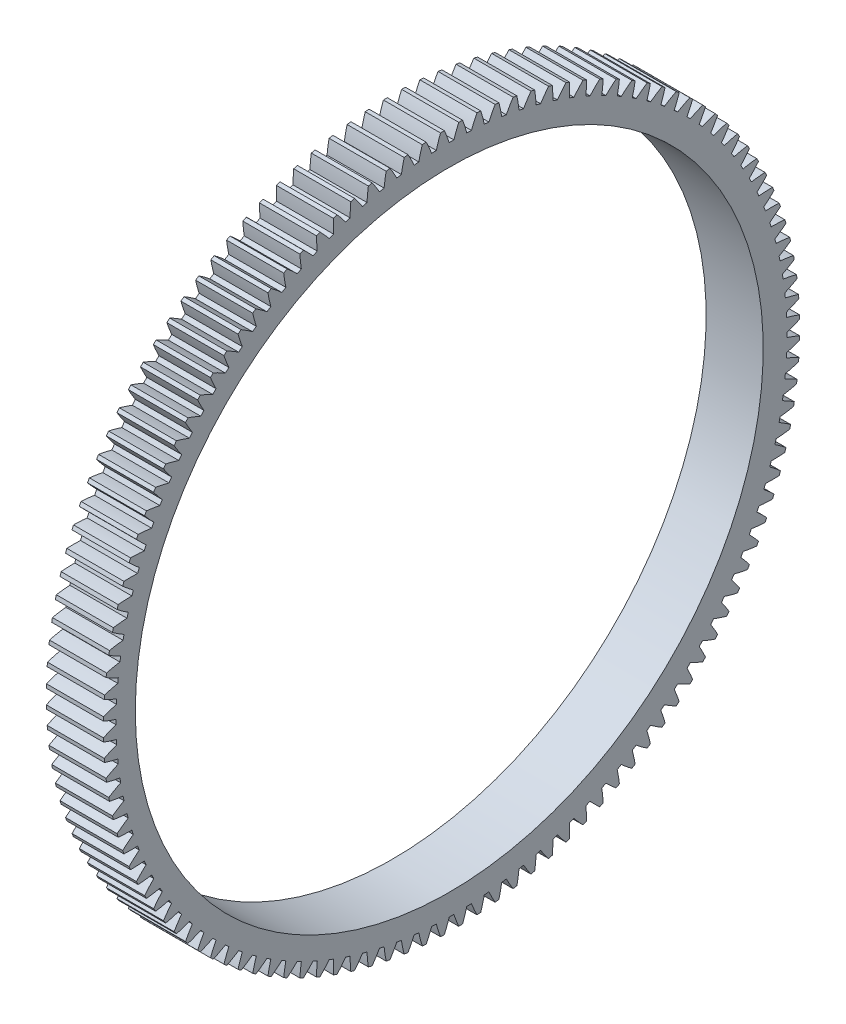
SolidWorks part; units mm, degrees
ref_plane "Plane1" through (0, 0, 0) normal (0, 0, 1) x (1, 0, 0)
ref_plane "Plane2" through (0, 0, 0) normal (0, 1, 0) x (1, 0, 0)
ref_plane "Plane3" through (0, 0, 0) normal (1, 0, 0) x (0, 0, -1)
other "Configuration Table"
sketch "HoldingSke" plane through (0, 0, 0) normal (0, 1, 0) x (1, 0, 0)
  line L0 (0, 0) -> (-0.5, -0.866)
  line L1 (-15, 0) -> (100, 0) construction
  line L2 (0, 0) -> (-2.1039, 2.3779)
  line L3 (0, 0) -> (-11.863, 4.5341)
  line L4 (0, 0) -> (-4.318, 7.479)
  line L5 (0, 0) -> (-46.8476, -17.4728)
  line L6 (0, 0) -> (-9.9476, -6.7116)
  line L7 (-2.1039, 2.3779) -> (8.6586, 51.2059)
  line L8 (-76.2, 54.61) -> (-76.1, 54.61)
  line L9 (-71.009, 38.7566) -> (-53.1078, 45.2721)
  line L10 (-76.2, 71.12) -> (104.1128, 71.12)
  line L11 (0, 0) -> (-12, 0)
  line L12 (-76.2, 101.6) -> (-76.162, 101.6)
  line L13 (24.9733, 27.94) -> (52.9518, 28.4284)
  line L14 (24.9733, 27.94) -> (24.9743, 27.94)
  line L15 (24.9733, 27.94) -> (100.4006, 29.5858)
  line L16 (-63.627, -1) -> (-12.827, -1)
  circle A0 centre (0, 0) radius 0.4
  circle A1 centre (0, 0) radius 37.5
  circle A2 centre (0, 0) radius 37.5
  circle A3 centre (0, 0) radius 0.4
  dimension "MHD" = 75
  dimension "Hub_dia" = 75
  dimension "Bore" = 0.8
  dimension "MBD" = 0.8
  dimension "Num_teeth" = 120
  dimension "Pitch" = 1
  dimension "Overall_len" = 50
  dimension "Show_teeth" = 120
  dimension "Thickness" = 12
  dimension "OAL" = 50.0001
  dimension "T_dim" = 0.1
  dimension "Ap" = 20
  dimension "H" = 19.05
  dimension "Pitch_radius" = 180.3128
  dimension "Width" = 12
  dimension "Backlash" = 0.038
  dimension "Addendum_fac" = 1
  dimension "Dedendum_fac" = 1.25
  dimension "Clearance_fac" = 0.25
  dimension "Dedendum_add" = 0.001
  dimension "Module" = 1
sketch "BasProSke" plane through (0, 0, 0) normal (0, 1, 0) x (1, 0, 0)
  line L0 (-10, 0) -> (60, 0) construction
  line L1 (0, 0) -> (0, 61)
  line L2 (0, 0) -> (12, 0)
  line L3 (12, 0) -> (12, 61)
  line L4 (12, 61) -> (0, 61)
  dimension "Thickness" = 12
  dimension "Diameter" = 122
revolve "Base-Revolve" add sketch "BasProSke" angle 360 about L0
sketch "TooCutSke" plane through (0, 0, 0) normal (1, 0, 0) x (0, 0, -1)
  line L1 (0, 0) -> (0, 107) construction
  line L2 (0, 0) -> (-0.8519, 59.994) construction
  line L3 (0, 0) -> (-3.141, 119.9503) construction
  line L4 (-0.8519, 59.994) -> (-1.5705, 59.9751) construction
  arc A0 (0.4107, 58.7476) -> (-0.4107, 58.7476) centre (0, 0) ccw
  arc A1 (1.2712, 61.0122) -> (-1.2712, 61.0122) centre (0, 0) ccw
  circle A2 centre (0, 0) radius 60 construction
  circle A3 centre (0, 0) radius 56.3816 construction
  arc A4 (-0.4107, 58.7476) -> (-1.2712, 61.0122) centre (-23.2473, 51.3658) ccw
  arc A5 (1.2712, 61.0122) -> (0.4107, 58.7476) centre (23.2473, 51.3658) ccw
  dimension "Root_dia" = 117.498
  dimension "Overcut_dia" = 122.0508
  dimension "Pitch_dia" = 120
  dimension "Base_dia" = 112.7631
  dimension "Flank_rad" = 24
  dimension "Half_ang" = 1.5
  dimension "Half_CT" = 0.7189
extrude "ToothCut" cut sketch "TooCutSke" along normal through all
fillet "Breaks" [suppressed] radius 0.02 tangent propagation no
fillet "RootFillets" [suppressed] radius 0.251
pattern_circular "TeethCuts" count 120 every 3 about axis through (-10, 0, 0) along (1, 0, 0) of "ToothCut", "RootFillets", "Breaks"
sketch "HubNeaOneSke" plane through (0, 0, 0) normal (-1, 0, 0) x (0, 0, 1)
  circle A0 centre (0, 0) radius 37.5
  dimension "Diameter" = 75
extrude "HubNearOne" [suppressed] add sketch "HubNeaOneSke" along normal blind 38.0001
sketch "HubNeaBotSke" plane through (0, 0, 0) normal (-1, 0, 0) x (0, 0, 1)
  circle A0 centre (0, 0) radius 37.5
  dimension "Diameter" = 75
extrude "HubNearBoth" [suppressed] add sketch "HubNeaBotSke" along normal blind 19
ref_plane "FarPln" through (12, 0, 0) normal (1, 0, 0) x (0, 0, -1)
sketch "HubFarSke" plane through (12, 0, 0) normal (1, 0, 0) x (0, 0, -1)
  circle A0 centre (0, 0) radius 37.5
  dimension "Diameter" = 75
extrude "HubFar" [suppressed] add sketch "HubFarSke" along normal blind 19
sketch "BorSke" plane through (0, 0, 0) normal (1, 0, 0) x (0, 0, -1)
  circle A0 centre (0, 0) radius 0.4
  dimension "Diameter" = 0.8
extrude "Bore" cut sketch "BorSke" along normal mid plane 100.0001
sketch "KeySke" plane through (0, 0, 0) normal (1, 0, 0) x (0, 0, -1)
  line L0 (-0.05, 0) -> (-0.05, 0.5)
  line L1 (-0.05, 0.5) -> (0.05, 0.5)
  line L2 (0.05, 0.5) -> (0.05, 0)
  line L3 (0, 0) -> (0, 34) construction
  line L4 (-0.05, 0) -> (0.05, 0)
  dimension "Offset" = 0.5
  dimension "Width" = 0.1
extrude "Keyway" [suppressed] cut sketch "KeySke" along normal mid plane 100.0001
pattern_circular "Keyway2" [suppressed] count 2 every 90 about axis through (-10, 0, 0) along (1, 0, 0) reverse direction yes
sketch "Sketch1" plane through (0, 0, 0) normal (-1, 0, 0) x (0, 0, 1)
  circle A0 centre (0.4, 0) radius 55
  circle A1 centre (0, 0) radius 0.4 construction
  dimension "D1" = 110
extrude "Cut-Extrude1" cut sketch "Sketch1" against normal blind 10
sketch "Sketch2" plane through (12, 0, 0) normal (1, 0, 0) x (0, 0, -1)
  arc A480 (-60.987, 1.2602) -> (-58.7476, 0.4107) centre (-51.3658, 23.2473) ccw
  arc A481 (-58.7476, 0.4107) -> (-58.7476, -0.4107) centre (0, 0) ccw
  arc A482 (-58.7476, -0.4107) -> (-60.987, -1.2602) centre (-51.3658, -23.2473) ccw
  arc A483 (-60.987, -1.2602) -> (-60.9694, -1.9333) centre (0, 0) ccw
  arc A484 (-60.9694, -1.9333) -> (-58.6885, -2.6645) centre (-52.5121, 20.5272) ccw
  arc A485 (-58.6885, -2.6645) -> (-58.6456, -3.4848) centre (0, 0) ccw
  arc A486 (-58.6456, -3.4848) -> (-60.8374, -4.4503) centre (-50.0787, -25.9037) ccw
  arc A487 (-60.8374, -4.4503) -> (-60.7846, -5.1216) centre (0, 0) ccw
  arc A488 (-60.7846, -5.1216) -> (-58.4687, -5.7323) centre (-53.5144, 17.7508) ccw
  arc A489 (-58.4687, -5.7323) -> (-58.3828, -6.5493) centre (0, 0) ccw
  arc A490 (-58.3828, -6.5493) -> (-60.5212, -7.6282) centre (-48.6544, -28.4891) ccw
  arc A491 (-60.5212, -7.6282) -> (-60.4333, -8.2958) centre (0, 0) ccw
  arc A492 (-60.4333, -8.2958) -> (-58.0885, -8.7845) centre (-54.3701, 14.9257) ccw
  arc A493 (-58.0885, -8.7845) -> (-57.96, -9.5958) centre (0, 0) ccw
  arc A494 (-57.96, -9.5958) -> (-60.039, -10.7851) centre (-47.0967, -30.9965) ccw
  arc A495 (-60.039, -10.7851) -> (-59.9163, -11.4473) centre (0, 0) ccw
  arc A496 (-59.9163, -11.4473) -> (-57.5492, -11.8126) centre (-55.0767, 12.0597) ccw
  arc A497 (-57.5492, -11.8126) -> (-57.3784, -12.616) centre (0, 0) ccw
  arc A498 (-57.3784, -12.616) -> (-59.3923, -13.9126) centre (-45.4099, -33.4188) ccw
  arc A499 (-59.3923, -13.9126) -> (-59.2351, -14.5673) centre (0, 0) ccw
  arc A500 (-59.2351, -14.5673) -> (-56.8521, -14.8083) centre (-55.6324, 9.1607) ccw
  arc A501 (-56.8521, -14.8083) -> (-56.6395, -15.6017) centre (0, 0) ccw
  arc A502 (-56.6395, -15.6017) -> (-58.5827, -17.0018) centre (-43.5987, -35.7496) ccw
  arc A503 (-58.5827, -17.0018) -> (-58.3915, -17.6475) centre (0, 0) ccw
  arc A504 (-58.3915, -17.6475) -> (-55.9992, -17.7634) centre (-56.0356, 6.2366) ccw
  arc A505 (-55.9992, -17.7634) -> (-55.7453, -18.5446) centre (0, 0) ccw
  arc A506 (-55.7453, -18.5446) -> (-57.6126, -20.0445) centre (-41.668, -37.9824) ccw
  arc A507 (-57.6126, -20.0445) -> (-57.3879, -20.6793) centre (0, 0) ccw
  arc A508 (-57.3879, -20.6793) -> (-54.9928, -20.6698) centre (-56.2852, 3.2954) ccw
  arc A509 (-54.9928, -20.6698) -> (-54.6984, -21.4367) centre (0, 0) ccw
  arc A510 (-54.6984, -21.4367) -> (-56.4846, -23.0323) centre (-39.623, -40.1111) ccw
  arc A511 (-56.4846, -23.0323) -> (-56.2269, -23.6544) centre (0, 0) ccw
  arc A512 (-56.2269, -23.6544) -> (-53.8356, -23.5196) centre (-56.3805, 0.3451) ccw
  arc A513 (-53.8356, -23.5196) -> (-53.5015, -24.27) centre (0, 0) ccw
  arc A514 (-53.5015, -24.27) -> (-55.2018, -25.9569) centre (-37.4695, -42.1298) ccw
  arc A515 (-55.2018, -25.9569) -> (-54.9119, -26.5647) centre (0, 0) ccw
  arc A516 (-54.9119, -26.5647) -> (-52.5309, -26.3049) centre (-56.3213, -2.6061) ccw
  arc A517 (-52.5309, -26.3049) -> (-52.158, -27.0368) centre (0, 0) ccw
  arc A518 (-52.158, -27.0368) -> (-53.7677, -28.8103) centre (-35.2132, -44.0331) ccw
  arc A519 (-53.7677, -28.8103) -> (-53.4464, -29.4021) centre (0, 0) ccw
  arc A520 (-53.4464, -29.4021) -> (-51.0822, -29.0181) centre (-56.1077, -5.5501) ccw
  arc A521 (-51.0822, -29.0181) -> (-50.6715, -29.7295) centre (0, 0) ccw
  arc A522 (-50.6715, -29.7295) -> (-52.1862, -31.5848) centre (-32.8604, -45.8156) ccw
  arc A523 (-52.1862, -31.5848) -> (-51.8343, -32.159) centre (0, 0) ccw
  arc A524 (-51.8343, -32.159) -> (-49.4935, -31.6518) centre (-55.7404, -8.479) ccw
  arc A525 (-49.4935, -31.6518) -> (-49.0462, -32.3407) centre (0, 0) ccw
  arc A526 (-49.0462, -32.3407) -> (-50.4616, -34.2728) centre (-30.4176, -47.4726) ccw
  arc A527 (-50.4616, -34.2728) -> (-50.0802, -34.8277) centre (0, 0) ccw
  arc A528 (-50.0802, -34.8277) -> (-47.7692, -34.1987) centre (-55.2202, -11.3846) ccw
  arc A529 (-47.7692, -34.1987) -> (-47.2864, -34.8632) centre (0, 0) ccw
  arc A530 (-47.2864, -34.8632) -> (-48.5988, -36.8668) centre (-27.8914, -48.9995) ccw
  arc A531 (-48.5988, -36.8668) -> (-48.1889, -37.401) centre (0, 0) ccw
  arc A532 (-48.1889, -37.401) -> (-45.9139, -36.6519) centre (-54.5487, -14.259) ccw
  arc A533 (-45.9139, -36.6519) -> (-45.397, -37.2902) centre (0, 0) ccw
  arc A534 (-45.397, -37.2902) -> (-46.6027, -39.3597) centre (-25.2887, -50.3921) ccw
  arc A535 (-46.6027, -39.3597) -> (-46.1654, -39.8718) centre (0, 0) ccw
  arc A536 (-46.1654, -39.8718) -> (-43.9328, -39.0046) centre (-53.7277, -17.0943) ccw
  arc A537 (-43.9328, -39.0046) -> (-43.3831, -39.615) centre (0, 0) ccw
  arc A538 (-43.3831, -39.615) -> (-44.4789, -41.7448) centre (-22.6167, -51.6465) ccw
  arc A539 (-44.4789, -41.7448) -> (-44.0154, -42.2332) centre (0, 0) ccw
  arc A540 (-44.0154, -42.2332) -> (-41.8312, -41.2504) centre (-52.7594, -19.8828) ccw
  arc A541 (-41.8312, -41.2504) -> (-41.2504, -41.8312) centre (0, 0) ccw
  arc A542 (-41.2504, -41.8312) -> (-42.2332, -44.0154) centre (-19.8828, -52.7594) ccw
  arc A543 (-42.2332, -44.0154) -> (-41.7448, -44.4789) centre (0, 0) ccw
  arc A544 (-41.7448, -44.4789) -> (-39.615, -43.3831) centre (-51.6465, -22.6167) ccw
  arc A545 (-39.615, -43.3831) -> (-39.0046, -43.9328) centre (0, 0) ccw
  arc A546 (-39.0046, -43.9328) -> (-39.8718, -46.1654) centre (-17.0943, -53.7277) ccw
  arc A547 (-39.8718, -46.1654) -> (-39.3597, -46.6027) centre (0, 0) ccw
  arc A548 (-39.3597, -46.6027) -> (-37.2902, -45.397) centre (-50.3921, -25.2887) ccw
  arc A549 (-37.2902, -45.397) -> (-36.6519, -45.9139) centre (0, 0) ccw
  arc A550 (-36.6519, -45.9139) -> (-37.401, -48.1889) centre (-14.259, -54.5487) ccw
  arc A551 (-37.401, -48.1889) -> (-36.8668, -48.5988) centre (0, 0) ccw
  arc A552 (-36.8668, -48.5988) -> (-34.8632, -47.2864) centre (-48.9995, -27.8914) ccw
  arc A553 (-34.8632, -47.2864) -> (-34.1987, -47.7692) centre (0, 0) ccw
  arc A554 (-34.1987, -47.7692) -> (-34.8277, -50.0802) centre (-11.3846, -55.2202) ccw
  arc A555 (-34.8277, -50.0802) -> (-34.2728, -50.4616) centre (0, 0) ccw
  arc A556 (-34.2728, -50.4616) -> (-32.3407, -49.0462) centre (-47.4726, -30.4176) ccw
  arc A557 (-32.3407, -49.0462) -> (-31.6518, -49.4935) centre (0, 0) ccw
  arc A558 (-31.6518, -49.4935) -> (-32.159, -51.8343) centre (-8.479, -55.7404) ccw
  arc A559 (-32.159, -51.8343) -> (-31.5848, -52.1862) centre (0, 0) ccw
  arc A560 (-31.5848, -52.1862) -> (-29.7295, -50.6715) centre (-45.8156, -32.8604) ccw
  arc A561 (-29.7295, -50.6715) -> (-29.0181, -51.0822) centre (0, 0) ccw
  arc A562 (-29.0181, -51.0822) -> (-29.4021, -53.4464) centre (-5.5501, -56.1077) ccw
  arc A563 (-29.4021, -53.4464) -> (-28.8103, -53.7677) centre (0, 0) ccw
  arc A564 (-28.8103, -53.7677) -> (-27.0368, -52.158) centre (-44.0331, -35.2132) ccw
  arc A565 (-27.0368, -52.158) -> (-26.3049, -52.5309) centre (0, 0) ccw
  arc A566 (-26.3049, -52.5309) -> (-26.5647, -54.9119) centre (-2.6061, -56.3213) ccw
  arc A567 (-26.5647, -54.9119) -> (-25.9569, -55.2018) centre (0, 0) ccw
  arc A568 (-25.9569, -55.2018) -> (-24.27, -53.5015) centre (-42.1298, -37.4695) ccw
  arc A569 (-24.27, -53.5015) -> (-23.5196, -53.8356) centre (0, 0) ccw
  arc A570 (-23.5196, -53.8356) -> (-23.6544, -56.2269) centre (0.3451, -56.3805) ccw
  arc A571 (-23.6544, -56.2269) -> (-23.0323, -56.4846) centre (0, 0) ccw
  arc A572 (-23.0323, -56.4846) -> (-21.4367, -54.6984) centre (-40.1111, -39.623) ccw
  arc A573 (-21.4367, -54.6984) -> (-20.6698, -54.9928) centre (0, 0) ccw
  arc A574 (-20.6698, -54.9928) -> (-20.6793, -57.3879) centre (3.2954, -56.2852) ccw
  arc A575 (-20.6793, -57.3879) -> (-20.0445, -57.6126) centre (0, 0) ccw
  arc A576 (-20.0445, -57.6126) -> (-18.5446, -55.7453) centre (-37.9824, -41.668) ccw
  arc A577 (-18.5446, -55.7453) -> (-17.7634, -55.9992) centre (0, 0) ccw
  arc A578 (-17.7634, -55.9992) -> (-17.6475, -58.3915) centre (6.2366, -56.0356) ccw
  arc A579 (-17.6475, -58.3915) -> (-17.0018, -58.5827) centre (0, 0) ccw
  arc A580 (-17.0018, -58.5827) -> (-15.6017, -56.6395) centre (-35.7496, -43.5987) ccw
  arc A581 (-15.6017, -56.6395) -> (-14.8083, -56.8521) centre (0, 0) ccw
  arc A582 (-14.8083, -56.8521) -> (-14.5673, -59.2351) centre (9.1607, -55.6324) ccw
  arc A583 (-14.5673, -59.2351) -> (-13.9126, -59.3923) centre (0, 0) ccw
  arc A584 (-13.9126, -59.3923) -> (-12.616, -57.3784) centre (-33.4188, -45.4099) ccw
  arc A585 (-12.616, -57.3784) -> (-11.8126, -57.5492) centre (0, 0) ccw
  arc A586 (-11.8126, -57.5492) -> (-11.4473, -59.9163) centre (12.0597, -55.0767) ccw
  arc A587 (-11.4473, -59.9163) -> (-10.7851, -60.039) centre (0, 0) ccw
  arc A588 (-10.7851, -60.039) -> (-9.5958, -57.96) centre (-30.9965, -47.0967) ccw
  arc A589 (-9.5958, -57.96) -> (-8.7845, -58.0885) centre (0, 0) ccw
  arc A590 (-8.7845, -58.0885) -> (-8.2958, -60.4333) centre (14.9257, -54.3701) ccw
  arc A591 (-8.2958, -60.4333) -> (-7.6282, -60.5212) centre (0, 0) ccw
  arc A592 (-7.6282, -60.5212) -> (-6.5493, -58.3828) centre (-28.4891, -48.6544) ccw
  arc A593 (-6.5493, -58.3828) -> (-5.7323, -58.4687) centre (0, 0) ccw
  arc A594 (-5.7323, -58.4687) -> (-5.1216, -60.7846) centre (17.7508, -53.5144) ccw
  arc A595 (-5.1216, -60.7846) -> (-4.4503, -60.8374) centre (0, 0) ccw
  arc A596 (-4.4503, -60.8374) -> (-3.4848, -58.6456) centre (-25.9037, -50.0787) ccw
  arc A597 (-3.4848, -58.6456) -> (-2.6645, -58.6885) centre (0, 0) ccw
  arc A598 (-2.6645, -58.6885) -> (-1.9333, -60.9694) centre (20.5272, -52.5121) ccw
  arc A599 (-1.9333, -60.9694) -> (-1.2602, -60.987) centre (0, 0) ccw
  arc A600 (-1.2602, -60.987) -> (-0.4107, -58.7476) centre (-23.2473, -51.3658) ccw
  arc A601 (-0.4107, -58.7476) -> (0.4107, -58.7476) centre (0, 0) ccw
  arc A602 (0.4107, -58.7476) -> (1.2602, -60.987) centre (23.2473, -51.3658) ccw
  arc A603 (1.2602, -60.987) -> (1.9333, -60.9694) centre (0, 0) ccw
  arc A604 (1.9333, -60.9694) -> (2.6645, -58.6885) centre (-20.5272, -52.5121) ccw
  arc A605 (2.6645, -58.6885) -> (3.4848, -58.6456) centre (0, 0) ccw
  arc A606 (3.4848, -58.6456) -> (4.4503, -60.8374) centre (25.9037, -50.0787) ccw
  arc A607 (4.4503, -60.8374) -> (5.1216, -60.7846) centre (0, 0) ccw
  arc A608 (5.1216, -60.7846) -> (5.7323, -58.4687) centre (-17.7508, -53.5144) ccw
  arc A609 (5.7323, -58.4687) -> (6.5493, -58.3828) centre (0, 0) ccw
  arc A610 (6.5493, -58.3828) -> (7.6282, -60.5212) centre (28.4891, -48.6544) ccw
  arc A611 (7.6282, -60.5212) -> (8.2958, -60.4333) centre (0, 0) ccw
  arc A612 (8.2958, -60.4333) -> (8.7845, -58.0885) centre (-14.9257, -54.3701) ccw
  arc A613 (8.7845, -58.0885) -> (9.5958, -57.96) centre (0, 0) ccw
  arc A614 (9.5958, -57.96) -> (10.7851, -60.039) centre (30.9965, -47.0967) ccw
  arc A615 (10.7851, -60.039) -> (11.4473, -59.9163) centre (0, 0) ccw
  arc A616 (11.4473, -59.9163) -> (11.8126, -57.5492) centre (-12.0597, -55.0767) ccw
  arc A617 (11.8126, -57.5492) -> (12.616, -57.3784) centre (0, 0) ccw
  arc A618 (12.616, -57.3784) -> (13.9126, -59.3923) centre (33.4188, -45.4099) ccw
  arc A619 (13.9126, -59.3923) -> (14.5673, -59.2351) centre (0, 0) ccw
  arc A620 (14.5673, -59.2351) -> (14.8083, -56.8521) centre (-9.1607, -55.6324) ccw
  arc A621 (14.8083, -56.8521) -> (15.6017, -56.6395) centre (0, 0) ccw
  arc A622 (15.6017, -56.6395) -> (17.0018, -58.5827) centre (35.7496, -43.5987) ccw
  arc A623 (17.0018, -58.5827) -> (17.6475, -58.3915) centre (0, 0) ccw
  arc A624 (17.6475, -58.3915) -> (17.7634, -55.9992) centre (-6.2366, -56.0356) ccw
  arc A625 (17.7634, -55.9992) -> (18.5446, -55.7453) centre (0, 0) ccw
  arc A626 (18.5446, -55.7453) -> (20.0445, -57.6126) centre (37.9824, -41.668) ccw
  arc A627 (20.0445, -57.6126) -> (20.6793, -57.3879) centre (0, 0) ccw
  arc A628 (20.6793, -57.3879) -> (20.6698, -54.9928) centre (-3.2954, -56.2852) ccw
  arc A629 (20.6698, -54.9928) -> (21.4367, -54.6984) centre (0, 0) ccw
  arc A630 (21.4367, -54.6984) -> (23.0323, -56.4846) centre (40.1111, -39.623) ccw
  arc A631 (23.0323, -56.4846) -> (23.6544, -56.2269) centre (0, 0) ccw
  arc A632 (23.6544, -56.2269) -> (23.5196, -53.8356) centre (-0.3451, -56.3805) ccw
  arc A633 (23.5196, -53.8356) -> (24.27, -53.5015) centre (0, 0) ccw
  arc A634 (24.27, -53.5015) -> (25.9569, -55.2018) centre (42.1298, -37.4695) ccw
  arc A635 (25.9569, -55.2018) -> (26.5647, -54.9119) centre (0, 0) ccw
  arc A636 (26.5647, -54.9119) -> (26.3049, -52.5309) centre (2.6061, -56.3213) ccw
  arc A637 (26.3049, -52.5309) -> (27.0368, -52.158) centre (0, 0) ccw
  arc A638 (27.0368, -52.158) -> (28.8103, -53.7677) centre (44.0331, -35.2132) ccw
  arc A639 (28.8103, -53.7677) -> (29.4021, -53.4464) centre (0, 0) ccw
  arc A640 (29.4021, -53.4464) -> (29.0181, -51.0822) centre (5.5501, -56.1077) ccw
  arc A641 (29.0181, -51.0822) -> (29.7295, -50.6715) centre (0, 0) ccw
  arc A642 (29.7295, -50.6715) -> (31.5848, -52.1862) centre (45.8156, -32.8604) ccw
  arc A643 (31.5848, -52.1862) -> (32.159, -51.8343) centre (0, 0) ccw
  arc A644 (32.159, -51.8343) -> (31.6518, -49.4935) centre (8.479, -55.7404) ccw
  arc A645 (31.6518, -49.4935) -> (32.3407, -49.0462) centre (0, 0) ccw
  arc A646 (32.3407, -49.0462) -> (34.2728, -50.4616) centre (47.4726, -30.4176) ccw
  arc A647 (34.2728, -50.4616) -> (34.8277, -50.0802) centre (0, 0) ccw
  arc A648 (34.8277, -50.0802) -> (34.1987, -47.7692) centre (11.3846, -55.2202) ccw
  arc A649 (34.1987, -47.7692) -> (34.8632, -47.2864) centre (0, 0) ccw
  arc A650 (34.8632, -47.2864) -> (36.8668, -48.5988) centre (48.9995, -27.8914) ccw
  arc A651 (36.8668, -48.5988) -> (37.401, -48.1889) centre (0, 0) ccw
  arc A652 (37.401, -48.1889) -> (36.6519, -45.9139) centre (14.259, -54.5487) ccw
  arc A653 (36.6519, -45.9139) -> (37.2902, -45.397) centre (0, 0) ccw
  arc A654 (37.2902, -45.397) -> (39.3597, -46.6027) centre (50.3921, -25.2887) ccw
  arc A655 (39.3597, -46.6027) -> (39.8718, -46.1654) centre (0, 0) ccw
  arc A656 (39.8718, -46.1654) -> (39.0046, -43.9328) centre (17.0943, -53.7277) ccw
  arc A657 (39.0046, -43.9328) -> (39.615, -43.3831) centre (0, 0) ccw
  arc A658 (39.615, -43.3831) -> (41.7448, -44.4789) centre (51.6465, -22.6167) ccw
  arc A659 (41.7448, -44.4789) -> (42.2332, -44.0154) centre (0, 0) ccw
  arc A660 (42.2332, -44.0154) -> (41.2504, -41.8312) centre (19.8828, -52.7594) ccw
  arc A661 (41.2504, -41.8312) -> (41.8312, -41.2504) centre (0, 0) ccw
  arc A662 (41.8312, -41.2504) -> (44.0154, -42.2332) centre (52.7594, -19.8828) ccw
  arc A663 (44.0154, -42.2332) -> (44.4789, -41.7448) centre (0, 0) ccw
  arc A664 (44.4789, -41.7448) -> (43.3831, -39.615) centre (22.6167, -51.6465) ccw
  arc A665 (43.3831, -39.615) -> (43.9328, -39.0046) centre (0, 0) ccw
  arc A666 (43.9328, -39.0046) -> (46.1654, -39.8718) centre (53.7277, -17.0943) ccw
  arc A667 (46.1654, -39.8718) -> (46.6027, -39.3597) centre (0, 0) ccw
  arc A668 (46.6027, -39.3597) -> (45.397, -37.2902) centre (25.2887, -50.3921) ccw
  arc A669 (45.397, -37.2902) -> (45.9139, -36.6519) centre (0, 0) ccw
  arc A670 (45.9139, -36.6519) -> (48.1889, -37.401) centre (54.5487, -14.259) ccw
  arc A671 (48.1889, -37.401) -> (48.5988, -36.8668) centre (0, 0) ccw
  arc A672 (48.5988, -36.8668) -> (47.2864, -34.8632) centre (27.8914, -48.9995) ccw
  arc A673 (47.2864, -34.8632) -> (47.7692, -34.1987) centre (0, 0) ccw
  arc A674 (47.7692, -34.1987) -> (50.0802, -34.8277) centre (55.2202, -11.3846) ccw
  arc A675 (50.0802, -34.8277) -> (50.4616, -34.2728) centre (0, 0) ccw
  arc A676 (50.4616, -34.2728) -> (49.0462, -32.3407) centre (30.4176, -47.4726) ccw
  arc A677 (49.0462, -32.3407) -> (49.4935, -31.6518) centre (0, 0) ccw
  arc A678 (49.4935, -31.6518) -> (51.8343, -32.159) centre (55.7404, -8.479) ccw
  arc A679 (51.8343, -32.159) -> (52.1862, -31.5848) centre (0, 0) ccw
  arc A680 (52.1862, -31.5848) -> (50.6715, -29.7295) centre (32.8604, -45.8156) ccw
  arc A681 (50.6715, -29.7295) -> (51.0822, -29.0181) centre (0, 0) ccw
  arc A682 (51.0822, -29.0181) -> (53.4464, -29.4021) centre (56.1077, -5.5501) ccw
  arc A683 (53.4464, -29.4021) -> (53.7677, -28.8103) centre (0, 0) ccw
  arc A684 (53.7677, -28.8103) -> (52.158, -27.0368) centre (35.2132, -44.0331) ccw
  arc A685 (52.158, -27.0368) -> (52.5309, -26.3049) centre (0, 0) ccw
  arc A686 (52.5309, -26.3049) -> (54.9119, -26.5647) centre (56.3213, -2.6061) ccw
  arc A687 (54.9119, -26.5647) -> (55.2018, -25.9569) centre (0, 0) ccw
  arc A688 (55.2018, -25.9569) -> (53.5015, -24.27) centre (37.4695, -42.1298) ccw
  arc A689 (53.5015, -24.27) -> (53.8356, -23.5196) centre (0, 0) ccw
  arc A690 (53.8356, -23.5196) -> (56.2269, -23.6544) centre (56.3805, 0.3451) ccw
  arc A691 (56.2269, -23.6544) -> (56.4846, -23.0323) centre (0, 0) ccw
  arc A692 (56.4846, -23.0323) -> (54.6984, -21.4367) centre (39.623, -40.1111) ccw
  arc A693 (54.6984, -21.4367) -> (54.9928, -20.6698) centre (0, 0) ccw
  arc A694 (54.9928, -20.6698) -> (57.3879, -20.6793) centre (56.2852, 3.2954) ccw
  arc A695 (57.3879, -20.6793) -> (57.6126, -20.0445) centre (0, 0) ccw
  arc A696 (57.6126, -20.0445) -> (55.7453, -18.5446) centre (41.668, -37.9824) ccw
  arc A697 (55.7453, -18.5446) -> (55.9992, -17.7634) centre (0, 0) ccw
  arc A698 (55.9992, -17.7634) -> (58.3915, -17.6475) centre (56.0356, 6.2366) ccw
  arc A699 (58.3915, -17.6475) -> (58.5827, -17.0018) centre (0, 0) ccw
  arc A700 (58.5827, -17.0018) -> (56.6395, -15.6017) centre (43.5987, -35.7496) ccw
  arc A701 (56.6395, -15.6017) -> (56.8521, -14.8083) centre (0, 0) ccw
  arc A702 (56.8521, -14.8083) -> (59.2351, -14.5673) centre (55.6324, 9.1607) ccw
  arc A703 (59.2351, -14.5673) -> (59.3923, -13.9126) centre (0, 0) ccw
  arc A704 (59.3923, -13.9126) -> (57.3784, -12.616) centre (45.4099, -33.4188) ccw
  arc A705 (57.3784, -12.616) -> (57.5492, -11.8126) centre (0, 0) ccw
  arc A706 (57.5492, -11.8126) -> (59.9163, -11.4473) centre (55.0767, 12.0597) ccw
  arc A707 (59.9163, -11.4473) -> (60.039, -10.7851) centre (0, 0) ccw
  arc A708 (60.039, -10.7851) -> (57.96, -9.5958) centre (47.0967, -30.9965) ccw
  arc A709 (57.96, -9.5958) -> (58.0885, -8.7845) centre (0, 0) ccw
  arc A710 (58.0885, -8.7845) -> (60.4333, -8.2958) centre (54.3701, 14.9257) ccw
  arc A711 (60.4333, -8.2958) -> (60.5212, -7.6282) centre (0, 0) ccw
  arc A712 (60.5212, -7.6282) -> (58.3828, -6.5493) centre (48.6544, -28.4891) ccw
  arc A713 (58.3828, -6.5493) -> (58.4687, -5.7323) centre (0, 0) ccw
  arc A714 (58.4687, -5.7323) -> (60.7846, -5.1216) centre (53.5144, 17.7508) ccw
  arc A715 (60.7846, -5.1216) -> (60.8374, -4.4503) centre (0, 0) ccw
  arc A716 (60.8374, -4.4503) -> (58.6456, -3.4848) centre (50.0787, -25.9037) ccw
  arc A717 (58.6456, -3.4848) -> (58.6885, -2.6645) centre (0, 0) ccw
  arc A718 (58.6885, -2.6645) -> (60.9694, -1.9333) centre (52.5121, 20.5272) ccw
  arc A719 (60.9694, -1.9333) -> (60.987, -1.2602) centre (0, 0) ccw
  arc A720 (60.987, -1.2602) -> (58.7476, -0.4107) centre (51.3658, -23.2473) ccw
  arc A721 (58.7476, -0.4107) -> (58.7476, 0.4107) centre (0, 0) ccw
  arc A722 (58.7476, 0.4107) -> (60.987, 1.2602) centre (51.3658, 23.2473) ccw
  arc A723 (60.987, 1.2602) -> (60.9694, 1.9333) centre (0, 0) ccw
  arc A724 (60.9694, 1.9333) -> (58.6885, 2.6645) centre (52.5121, -20.5272) ccw
  arc A725 (58.6885, 2.6645) -> (58.6456, 3.4848) centre (0, 0) ccw
  arc A726 (58.6456, 3.4848) -> (60.8374, 4.4503) centre (50.0787, 25.9037) ccw
  arc A727 (60.8374, 4.4503) -> (60.7846, 5.1216) centre (0, 0) ccw
  arc A728 (60.7846, 5.1216) -> (58.4687, 5.7323) centre (53.5144, -17.7508) ccw
  arc A729 (58.4687, 5.7323) -> (58.3828, 6.5493) centre (0, 0) ccw
  arc A730 (58.3828, 6.5493) -> (60.5212, 7.6282) centre (48.6544, 28.4891) ccw
  arc A731 (60.5212, 7.6282) -> (60.4333, 8.2958) centre (0, 0) ccw
  arc A732 (60.4333, 8.2958) -> (58.0885, 8.7845) centre (54.3701, -14.9257) ccw
  arc A733 (58.0885, 8.7845) -> (57.96, 9.5958) centre (0, 0) ccw
  arc A734 (57.96, 9.5958) -> (60.039, 10.7851) centre (47.0967, 30.9965) ccw
  arc A735 (60.039, 10.7851) -> (59.9163, 11.4473) centre (0, 0) ccw
  arc A736 (59.9163, 11.4473) -> (57.5492, 11.8126) centre (55.0767, -12.0597) ccw
  arc A737 (57.5492, 11.8126) -> (57.3784, 12.616) centre (0, 0) ccw
  arc A738 (57.3784, 12.616) -> (59.3923, 13.9126) centre (45.4099, 33.4188) ccw
  arc A739 (59.3923, 13.9126) -> (59.2351, 14.5673) centre (0, 0) ccw
  arc A740 (59.2351, 14.5673) -> (56.8521, 14.8083) centre (55.6324, -9.1607) ccw
  arc A741 (56.8521, 14.8083) -> (56.6395, 15.6017) centre (0, 0) ccw
  arc A742 (56.6395, 15.6017) -> (58.5827, 17.0018) centre (43.5987, 35.7496) ccw
  arc A743 (58.5827, 17.0018) -> (58.3915, 17.6475) centre (0, 0) ccw
  arc A744 (58.3915, 17.6475) -> (55.9992, 17.7634) centre (56.0356, -6.2366) ccw
  arc A745 (55.9992, 17.7634) -> (55.7453, 18.5446) centre (0, 0) ccw
  arc A746 (55.7453, 18.5446) -> (57.6126, 20.0445) centre (41.668, 37.9824) ccw
  arc A747 (57.6126, 20.0445) -> (57.3879, 20.6793) centre (0, 0) ccw
  arc A748 (57.3879, 20.6793) -> (54.9928, 20.6698) centre (56.2852, -3.2954) ccw
  arc A749 (54.9928, 20.6698) -> (54.6984, 21.4367) centre (0, 0) ccw
  arc A750 (54.6984, 21.4367) -> (56.4846, 23.0323) centre (39.623, 40.1111) ccw
  arc A751 (56.4846, 23.0323) -> (56.2269, 23.6544) centre (0, 0) ccw
  arc A752 (56.2269, 23.6544) -> (53.8356, 23.5196) centre (56.3805, -0.3451) ccw
  arc A753 (53.8356, 23.5196) -> (53.5015, 24.27) centre (0, 0) ccw
  arc A754 (53.5015, 24.27) -> (55.2018, 25.9569) centre (37.4695, 42.1298) ccw
  arc A755 (55.2018, 25.9569) -> (54.9119, 26.5647) centre (0, 0) ccw
  arc A756 (54.9119, 26.5647) -> (52.5309, 26.3049) centre (56.3213, 2.6061) ccw
  arc A757 (52.5309, 26.3049) -> (52.158, 27.0368) centre (0, 0) ccw
  arc A758 (52.158, 27.0368) -> (53.7677, 28.8103) centre (35.2132, 44.0331) ccw
  arc A759 (53.7677, 28.8103) -> (53.4464, 29.4021) centre (0, 0) ccw
  arc A760 (53.4464, 29.4021) -> (51.0822, 29.0181) centre (56.1077, 5.5501) ccw
  arc A761 (51.0822, 29.0181) -> (50.6715, 29.7295) centre (0, 0) ccw
  arc A762 (50.6715, 29.7295) -> (52.1862, 31.5848) centre (32.8604, 45.8156) ccw
  arc A763 (52.1862, 31.5848) -> (51.8343, 32.159) centre (0, 0) ccw
  arc A764 (51.8343, 32.159) -> (49.4935, 31.6518) centre (55.7404, 8.479) ccw
  arc A765 (49.4935, 31.6518) -> (49.0462, 32.3407) centre (0, 0) ccw
  arc A766 (49.0462, 32.3407) -> (50.4616, 34.2728) centre (30.4176, 47.4726) ccw
  arc A767 (50.4616, 34.2728) -> (50.0802, 34.8277) centre (0, 0) ccw
  arc A768 (50.0802, 34.8277) -> (47.7692, 34.1987) centre (55.2202, 11.3846) ccw
  arc A769 (47.7692, 34.1987) -> (47.2864, 34.8632) centre (0, 0) ccw
  arc A770 (47.2864, 34.8632) -> (48.5988, 36.8668) centre (27.8914, 48.9995) ccw
  arc A771 (48.5988, 36.8668) -> (48.1889, 37.401) centre (0, 0) ccw
  arc A772 (48.1889, 37.401) -> (45.9139, 36.6519) centre (54.5487, 14.259) ccw
  arc A773 (45.9139, 36.6519) -> (45.397, 37.2902) centre (0, 0) ccw
  arc A774 (45.397, 37.2902) -> (46.6027, 39.3597) centre (25.2887, 50.3921) ccw
  arc A775 (46.6027, 39.3597) -> (46.1654, 39.8718) centre (0, 0) ccw
  arc A776 (46.1654, 39.8718) -> (43.9328, 39.0046) centre (53.7277, 17.0943) ccw
  arc A777 (43.9328, 39.0046) -> (43.3831, 39.615) centre (0, 0) ccw
  arc A778 (43.3831, 39.615) -> (44.4789, 41.7448) centre (22.6167, 51.6465) ccw
  arc A779 (44.4789, 41.7448) -> (44.0154, 42.2332) centre (0, 0) ccw
  arc A780 (44.0154, 42.2332) -> (41.8312, 41.2504) centre (52.7594, 19.8828) ccw
  arc A781 (41.8312, 41.2504) -> (41.2504, 41.8312) centre (0, 0) ccw
  arc A782 (41.2504, 41.8312) -> (42.2332, 44.0154) centre (19.8828, 52.7594) ccw
  arc A783 (42.2332, 44.0154) -> (41.7448, 44.4789) centre (0, 0) ccw
  arc A784 (41.7448, 44.4789) -> (39.615, 43.3831) centre (51.6465, 22.6167) ccw
  arc A785 (39.615, 43.3831) -> (39.0046, 43.9328) centre (0, 0) ccw
  arc A786 (39.0046, 43.9328) -> (39.8718, 46.1654) centre (17.0943, 53.7277) ccw
  arc A787 (39.8718, 46.1654) -> (39.3597, 46.6027) centre (0, 0) ccw
  arc A788 (39.3597, 46.6027) -> (37.2902, 45.397) centre (50.3921, 25.2887) ccw
  arc A789 (37.2902, 45.397) -> (36.6519, 45.9139) centre (0, 0) ccw
  arc A790 (36.6519, 45.9139) -> (37.401, 48.1889) centre (14.259, 54.5487) ccw
  arc A791 (37.401, 48.1889) -> (36.8668, 48.5988) centre (0, 0) ccw
  arc A792 (36.8668, 48.5988) -> (34.8632, 47.2864) centre (48.9995, 27.8914) ccw
  arc A793 (34.8632, 47.2864) -> (34.1987, 47.7692) centre (0, 0) ccw
  arc A794 (34.1987, 47.7692) -> (34.8277, 50.0802) centre (11.3846, 55.2202) ccw
  arc A795 (34.8277, 50.0802) -> (34.2728, 50.4616) centre (0, 0) ccw
  arc A796 (34.2728, 50.4616) -> (32.3407, 49.0462) centre (47.4726, 30.4176) ccw
  arc A797 (32.3407, 49.0462) -> (31.6518, 49.4935) centre (0, 0) ccw
  arc A798 (31.6518, 49.4935) -> (32.159, 51.8343) centre (8.479, 55.7404) ccw
  arc A799 (32.159, 51.8343) -> (31.5848, 52.1862) centre (0, 0) ccw
  arc A800 (31.5848, 52.1862) -> (29.7295, 50.6715) centre (45.8156, 32.8604) ccw
  arc A801 (29.7295, 50.6715) -> (29.0181, 51.0822) centre (0, 0) ccw
  arc A802 (29.0181, 51.0822) -> (29.4021, 53.4464) centre (5.5501, 56.1077) ccw
  arc A803 (29.4021, 53.4464) -> (28.8103, 53.7677) centre (0, 0) ccw
  arc A804 (28.8103, 53.7677) -> (27.0368, 52.158) centre (44.0331, 35.2132) ccw
  arc A805 (27.0368, 52.158) -> (26.3049, 52.5309) centre (0, 0) ccw
  arc A806 (26.3049, 52.5309) -> (26.5647, 54.9119) centre (2.6061, 56.3213) ccw
  arc A807 (26.5647, 54.9119) -> (25.9569, 55.2018) centre (0, 0) ccw
  arc A808 (25.9569, 55.2018) -> (24.27, 53.5015) centre (42.1298, 37.4695) ccw
  arc A809 (24.27, 53.5015) -> (23.5196, 53.8356) centre (0, 0) ccw
  arc A810 (23.5196, 53.8356) -> (23.6544, 56.2269) centre (-0.3451, 56.3805) ccw
  arc A811 (23.6544, 56.2269) -> (23.0323, 56.4846) centre (0, 0) ccw
  arc A812 (23.0323, 56.4846) -> (21.4367, 54.6984) centre (40.1111, 39.623) ccw
  arc A813 (21.4367, 54.6984) -> (20.6698, 54.9928) centre (0, 0) ccw
  arc A814 (20.6698, 54.9928) -> (20.6793, 57.3879) centre (-3.2954, 56.2852) ccw
  arc A815 (20.6793, 57.3879) -> (20.0445, 57.6126) centre (0, 0) ccw
  arc A816 (20.0445, 57.6126) -> (18.5446, 55.7453) centre (37.9824, 41.668) ccw
  arc A817 (18.5446, 55.7453) -> (17.7634, 55.9992) centre (0, 0) ccw
  arc A818 (17.7634, 55.9992) -> (17.6475, 58.3915) centre (-6.2366, 56.0356) ccw
  arc A819 (17.6475, 58.3915) -> (17.0018, 58.5827) centre (0, 0) ccw
  arc A820 (17.0018, 58.5827) -> (15.6017, 56.6395) centre (35.7496, 43.5987) ccw
  arc A821 (15.6017, 56.6395) -> (14.8083, 56.8521) centre (0, 0) ccw
  arc A822 (14.8083, 56.8521) -> (14.5673, 59.2351) centre (-9.1607, 55.6324) ccw
  arc A823 (14.5673, 59.2351) -> (13.9126, 59.3923) centre (0, 0) ccw
  arc A824 (13.9126, 59.3923) -> (12.616, 57.3784) centre (33.4188, 45.4099) ccw
  arc A825 (12.616, 57.3784) -> (11.8126, 57.5492) centre (0, 0) ccw
  arc A826 (11.8126, 57.5492) -> (11.4473, 59.9163) centre (-12.0597, 55.0767) ccw
  arc A827 (11.4473, 59.9163) -> (10.7851, 60.039) centre (0, 0) ccw
  arc A828 (10.7851, 60.039) -> (9.5958, 57.96) centre (30.9965, 47.0967) ccw
  arc A829 (9.5958, 57.96) -> (8.7845, 58.0885) centre (0, 0) ccw
  arc A830 (8.7845, 58.0885) -> (8.2958, 60.4333) centre (-14.9257, 54.3701) ccw
  arc A831 (8.2958, 60.4333) -> (7.6282, 60.5212) centre (0, 0) ccw
  arc A832 (7.6282, 60.5212) -> (6.5493, 58.3828) centre (28.4891, 48.6544) ccw
  arc A833 (6.5493, 58.3828) -> (5.7323, 58.4687) centre (0, 0) ccw
  arc A834 (5.7323, 58.4687) -> (5.1216, 60.7846) centre (-17.7508, 53.5144) ccw
  arc A835 (5.1216, 60.7846) -> (4.4503, 60.8374) centre (0, 0) ccw
  arc A836 (4.4503, 60.8374) -> (3.4848, 58.6456) centre (25.9037, 50.0787) ccw
  arc A837 (3.4848, 58.6456) -> (2.6645, 58.6885) centre (0, 0) ccw
  arc A838 (2.6645, 58.6885) -> (1.9333, 60.9694) centre (-20.5272, 52.5121) ccw
  arc A839 (1.9333, 60.9694) -> (1.2602, 60.987) centre (0, 0) ccw
  arc A840 (1.2602, 60.987) -> (0.4107, 58.7476) centre (23.2473, 51.3658) ccw
  arc A841 (0.4107, 58.7476) -> (-0.4107, 58.7476) centre (0, 0) ccw
  arc A842 (-0.4107, 58.7476) -> (-1.2602, 60.987) centre (-23.2473, 51.3658) ccw
  arc A843 (-1.2602, 60.987) -> (-1.9333, 60.9694) centre (0, 0) ccw
  arc A844 (-1.9333, 60.9694) -> (-2.6645, 58.6885) centre (20.5272, 52.5121) ccw
  arc A845 (-2.6645, 58.6885) -> (-3.4848, 58.6456) centre (0, 0) ccw
  arc A846 (-3.4848, 58.6456) -> (-4.4503, 60.8374) centre (-25.9037, 50.0787) ccw
  arc A847 (-4.4503, 60.8374) -> (-5.1216, 60.7846) centre (0, 0) ccw
  arc A848 (-5.1216, 60.7846) -> (-5.7323, 58.4687) centre (17.7508, 53.5144) ccw
  arc A849 (-5.7323, 58.4687) -> (-6.5493, 58.3828) centre (0, 0) ccw
  arc A850 (-6.5493, 58.3828) -> (-7.6282, 60.5212) centre (-28.4891, 48.6544) ccw
  arc A851 (-7.6282, 60.5212) -> (-8.2958, 60.4333) centre (0, 0) ccw
  arc A852 (-8.2958, 60.4333) -> (-8.7845, 58.0885) centre (14.9257, 54.3701) ccw
  arc A853 (-8.7845, 58.0885) -> (-9.5958, 57.96) centre (0, 0) ccw
  arc A854 (-9.5958, 57.96) -> (-10.7851, 60.039) centre (-30.9965, 47.0967) ccw
  arc A855 (-10.7851, 60.039) -> (-11.4473, 59.9163) centre (0, 0) ccw
  arc A856 (-11.4473, 59.9163) -> (-11.8126, 57.5492) centre (12.0597, 55.0767) ccw
  arc A857 (-11.8126, 57.5492) -> (-12.616, 57.3784) centre (0, 0) ccw
  arc A858 (-12.616, 57.3784) -> (-13.9126, 59.3923) centre (-33.4188, 45.4099) ccw
  arc A859 (-13.9126, 59.3923) -> (-14.5673, 59.2351) centre (0, 0) ccw
  arc A860 (-14.5673, 59.2351) -> (-14.8083, 56.8521) centre (9.1607, 55.6324) ccw
  arc A861 (-14.8083, 56.8521) -> (-15.6017, 56.6395) centre (0, 0) ccw
  arc A862 (-15.6017, 56.6395) -> (-17.0018, 58.5827) centre (-35.7496, 43.5987) ccw
  arc A863 (-17.0018, 58.5827) -> (-17.6475, 58.3915) centre (0, 0) ccw
  arc A864 (-17.6475, 58.3915) -> (-17.7634, 55.9992) centre (6.2366, 56.0356) ccw
  arc A865 (-17.7634, 55.9992) -> (-18.5446, 55.7453) centre (0, 0) ccw
  arc A866 (-18.5446, 55.7453) -> (-20.0445, 57.6126) centre (-37.9824, 41.668) ccw
  arc A867 (-20.0445, 57.6126) -> (-20.6793, 57.3879) centre (0, 0) ccw
  arc A868 (-20.6793, 57.3879) -> (-20.6698, 54.9928) centre (3.2954, 56.2852) ccw
  arc A869 (-20.6698, 54.9928) -> (-21.4367, 54.6984) centre (0, 0) ccw
  arc A870 (-21.4367, 54.6984) -> (-23.0323, 56.4846) centre (-40.1111, 39.623) ccw
  arc A871 (-23.0323, 56.4846) -> (-23.6544, 56.2269) centre (0, 0) ccw
  arc A872 (-23.6544, 56.2269) -> (-23.5196, 53.8356) centre (0.3451, 56.3805) ccw
  arc A873 (-23.5196, 53.8356) -> (-24.27, 53.5015) centre (0, 0) ccw
  arc A874 (-24.27, 53.5015) -> (-25.9569, 55.2018) centre (-42.1298, 37.4695) ccw
  arc A875 (-25.9569, 55.2018) -> (-26.5647, 54.9119) centre (0, 0) ccw
  arc A876 (-26.5647, 54.9119) -> (-26.3049, 52.5309) centre (-2.6061, 56.3213) ccw
  arc A877 (-26.3049, 52.5309) -> (-27.0368, 52.158) centre (0, 0) ccw
  arc A878 (-27.0368, 52.158) -> (-28.8103, 53.7677) centre (-44.0331, 35.2132) ccw
  arc A879 (-28.8103, 53.7677) -> (-29.4021, 53.4464) centre (0, 0) ccw
  arc A880 (-29.4021, 53.4464) -> (-29.0181, 51.0822) centre (-5.5501, 56.1077) ccw
  arc A881 (-29.0181, 51.0822) -> (-29.7295, 50.6715) centre (0, 0) ccw
  arc A882 (-29.7295, 50.6715) -> (-31.5848, 52.1862) centre (-45.8156, 32.8604) ccw
  arc A883 (-31.5848, 52.1862) -> (-32.159, 51.8343) centre (0, 0) ccw
  arc A884 (-32.159, 51.8343) -> (-31.6518, 49.4935) centre (-8.479, 55.7404) ccw
  arc A885 (-31.6518, 49.4935) -> (-32.3407, 49.0462) centre (0, 0) ccw
  arc A886 (-32.3407, 49.0462) -> (-34.2728, 50.4616) centre (-47.4726, 30.4176) ccw
  arc A887 (-34.2728, 50.4616) -> (-34.8277, 50.0802) centre (0, 0) ccw
  arc A888 (-34.8277, 50.0802) -> (-34.1987, 47.7692) centre (-11.3846, 55.2202) ccw
  arc A889 (-34.1987, 47.7692) -> (-34.8632, 47.2864) centre (0, 0) ccw
  arc A890 (-34.8632, 47.2864) -> (-36.8668, 48.5988) centre (-48.9995, 27.8914) ccw
  arc A891 (-36.8668, 48.5988) -> (-37.401, 48.1889) centre (0, 0) ccw
  arc A892 (-37.401, 48.1889) -> (-36.6519, 45.9139) centre (-14.259, 54.5487) ccw
  arc A893 (-36.6519, 45.9139) -> (-37.2902, 45.397) centre (0, 0) ccw
  arc A894 (-37.2902, 45.397) -> (-39.3597, 46.6027) centre (-50.3921, 25.2887) ccw
  arc A895 (-39.3597, 46.6027) -> (-39.8718, 46.1654) centre (0, 0) ccw
  arc A896 (-39.8718, 46.1654) -> (-39.0046, 43.9328) centre (-17.0943, 53.7277) ccw
  arc A897 (-39.0046, 43.9328) -> (-39.615, 43.3831) centre (0, 0) ccw
  arc A898 (-39.615, 43.3831) -> (-41.7448, 44.4789) centre (-51.6465, 22.6167) ccw
  arc A899 (-41.7448, 44.4789) -> (-42.2332, 44.0154) centre (0, 0) ccw
  arc A900 (-42.2332, 44.0154) -> (-41.2504, 41.8312) centre (-19.8828, 52.7594) ccw
  arc A901 (-41.2504, 41.8312) -> (-41.8312, 41.2504) centre (0, 0) ccw
  arc A902 (-41.8312, 41.2504) -> (-44.0154, 42.2332) centre (-52.7594, 19.8828) ccw
  arc A903 (-44.0154, 42.2332) -> (-44.4789, 41.7448) centre (0, 0) ccw
  arc A904 (-44.4789, 41.7448) -> (-43.3831, 39.615) centre (-22.6167, 51.6465) ccw
  arc A905 (-43.3831, 39.615) -> (-43.9328, 39.0046) centre (0, 0) ccw
  arc A906 (-43.9328, 39.0046) -> (-46.1654, 39.8718) centre (-53.7277, 17.0943) ccw
  arc A907 (-46.1654, 39.8718) -> (-46.6027, 39.3597) centre (0, 0) ccw
  arc A908 (-46.6027, 39.3597) -> (-45.397, 37.2902) centre (-25.2887, 50.3921) ccw
  arc A909 (-45.397, 37.2902) -> (-45.9139, 36.6519) centre (0, 0) ccw
  arc A910 (-45.9139, 36.6519) -> (-48.1889, 37.401) centre (-54.5487, 14.259) ccw
  arc A911 (-48.1889, 37.401) -> (-48.5988, 36.8668) centre (0, 0) ccw
  arc A912 (-48.5988, 36.8668) -> (-47.2864, 34.8632) centre (-27.8914, 48.9995) ccw
  arc A913 (-47.2864, 34.8632) -> (-47.7692, 34.1987) centre (0, 0) ccw
  arc A914 (-47.7692, 34.1987) -> (-50.0802, 34.8277) centre (-55.2202, 11.3846) ccw
  arc A915 (-50.0802, 34.8277) -> (-50.4616, 34.2728) centre (0, 0) ccw
  arc A916 (-50.4616, 34.2728) -> (-49.0462, 32.3407) centre (-30.4176, 47.4726) ccw
  arc A917 (-49.0462, 32.3407) -> (-49.4935, 31.6518) centre (0, 0) ccw
  arc A918 (-49.4935, 31.6518) -> (-51.8343, 32.159) centre (-55.7404, 8.479) ccw
  arc A919 (-51.8343, 32.159) -> (-52.1862, 31.5848) centre (0, 0) ccw
  arc A920 (-52.1862, 31.5848) -> (-50.6715, 29.7295) centre (-32.8604, 45.8156) ccw
  arc A921 (-50.6715, 29.7295) -> (-51.0822, 29.0181) centre (0, 0) ccw
  arc A922 (-51.0822, 29.0181) -> (-53.4464, 29.4021) centre (-56.1077, 5.5501) ccw
  arc A923 (-53.4464, 29.4021) -> (-53.7677, 28.8103) centre (0, 0) ccw
  arc A924 (-53.7677, 28.8103) -> (-52.158, 27.0368) centre (-35.2132, 44.0331) ccw
  arc A925 (-52.158, 27.0368) -> (-52.5309, 26.3049) centre (0, 0) ccw
  arc A926 (-52.5309, 26.3049) -> (-54.9119, 26.5647) centre (-56.3213, 2.6061) ccw
  arc A927 (-54.9119, 26.5647) -> (-55.2018, 25.9569) centre (0, 0) ccw
  arc A928 (-55.2018, 25.9569) -> (-53.5015, 24.27) centre (-37.4695, 42.1298) ccw
  arc A929 (-53.5015, 24.27) -> (-53.8356, 23.5196) centre (0, 0) ccw
  arc A930 (-53.8356, 23.5196) -> (-56.2269, 23.6544) centre (-56.3805, -0.3451) ccw
  arc A931 (-56.2269, 23.6544) -> (-56.4846, 23.0323) centre (0, 0) ccw
  arc A932 (-56.4846, 23.0323) -> (-54.6984, 21.4367) centre (-39.623, 40.1111) ccw
  arc A933 (-54.6984, 21.4367) -> (-54.9928, 20.6698) centre (0, 0) ccw
  arc A934 (-54.9928, 20.6698) -> (-57.3879, 20.6793) centre (-56.2852, -3.2954) ccw
  arc A935 (-57.3879, 20.6793) -> (-57.6126, 20.0445) centre (0, 0) ccw
  arc A936 (-57.6126, 20.0445) -> (-55.7453, 18.5446) centre (-41.668, 37.9824) ccw
  arc A937 (-55.7453, 18.5446) -> (-55.9992, 17.7634) centre (0, 0) ccw
  arc A938 (-55.9992, 17.7634) -> (-58.3915, 17.6475) centre (-56.0356, -6.2366) ccw
  arc A939 (-58.3915, 17.6475) -> (-58.5827, 17.0018) centre (0, 0) ccw
  arc A940 (-58.5827, 17.0018) -> (-56.6395, 15.6017) centre (-43.5987, 35.7496) ccw
  arc A941 (-56.6395, 15.6017) -> (-56.8521, 14.8083) centre (0, 0) ccw
  arc A942 (-56.8521, 14.8083) -> (-59.2351, 14.5673) centre (-55.6324, -9.1607) ccw
  arc A943 (-59.2351, 14.5673) -> (-59.3923, 13.9126) centre (0, 0) ccw
  arc A944 (-59.3923, 13.9126) -> (-57.3784, 12.616) centre (-45.4099, 33.4188) ccw
  arc A945 (-57.3784, 12.616) -> (-57.5492, 11.8126) centre (0, 0) ccw
  arc A946 (-57.5492, 11.8126) -> (-59.9163, 11.4473) centre (-55.0767, -12.0597) ccw
  arc A947 (-59.9163, 11.4473) -> (-60.039, 10.7851) centre (0, 0) ccw
  arc A948 (-60.039, 10.7851) -> (-57.96, 9.5958) centre (-47.0967, 30.9965) ccw
  arc A949 (-57.96, 9.5958) -> (-58.0885, 8.7845) centre (0, 0) ccw
  arc A950 (-58.0885, 8.7845) -> (-60.4333, 8.2958) centre (-54.3701, -14.9257) ccw
  arc A951 (-60.4333, 8.2958) -> (-60.5212, 7.6282) centre (0, 0) ccw
  arc A952 (-60.5212, 7.6282) -> (-58.3828, 6.5493) centre (-48.6544, 28.4891) ccw
  arc A953 (-58.3828, 6.5493) -> (-58.4687, 5.7323) centre (0, 0) ccw
  arc A954 (-58.4687, 5.7323) -> (-60.7846, 5.1216) centre (-53.5144, -17.7508) ccw
  arc A955 (-60.7846, 5.1216) -> (-60.8374, 4.4503) centre (0, 0) ccw
  arc A956 (-60.8374, 4.4503) -> (-58.6456, 3.4848) centre (-50.0787, 25.9037) ccw
  arc A957 (-58.6456, 3.4848) -> (-58.6885, 2.6645) centre (0, 0) ccw
  arc A958 (-58.6885, 2.6645) -> (-60.9694, 1.9333) centre (-52.5121, -20.5272) ccw
  arc A959 (-60.9694, 1.9333) -> (-60.987, 1.2602) centre (0, 0) ccw
  arc A960 (-60.987, 1.2602) -> (-58.7476, 0.4107) centre (-51.3658, 23.2473) ccw
  arc A961 (-58.7476, 0.4107) -> (-58.7476, -0.4107) centre (0, 0) ccw
  arc A962 (-58.7476, -0.4107) -> (-60.987, -1.2602) centre (-51.3658, -23.2473) ccw
  arc A963 (-60.987, -1.2602) -> (-60.9694, -1.9333) centre (0, 0) ccw
  arc A964 (-60.9694, -1.9333) -> (-58.6885, -2.6645) centre (-52.5121, 20.5272) ccw
  arc A965 (-58.6885, -2.6645) -> (-58.6456, -3.4848) centre (0, 0) ccw
  arc A966 (-58.6456, -3.4848) -> (-60.8374, -4.4503) centre (-50.0787, -25.9037) ccw
  arc A967 (-60.8374, -4.4503) -> (-60.7846, -5.1216) centre (0, 0) ccw
  arc A968 (-60.7846, -5.1216) -> (-58.4687, -5.7323) centre (-53.5144, 17.7508) ccw
  arc A969 (-58.4687, -5.7323) -> (-58.3828, -6.5493) centre (0, 0) ccw
  arc A970 (-58.3828, -6.5493) -> (-60.5212, -7.6282) centre (-48.6544, -28.4891) ccw
  arc A971 (-60.5212, -7.6282) -> (-60.4333, -8.2958) centre (0, 0) ccw
  arc A972 (-60.4333, -8.2958) -> (-58.0885, -8.7845) centre (-54.3701, 14.9257) ccw
  arc A973 (-58.0885, -8.7845) -> (-57.96, -9.5958) centre (0, 0) ccw
  arc A974 (-57.96, -9.5958) -> (-60.039, -10.7851) centre (-47.0967, -30.9965) ccw
  arc A975 (-60.039, -10.7851) -> (-59.9163, -11.4473) centre (0, 0) ccw
  arc A976 (-59.9163, -11.4473) -> (-57.5492, -11.8126) centre (-55.0767, 12.0597) ccw
  arc A977 (-57.5492, -11.8126) -> (-57.3784, -12.616) centre (0, 0) ccw
  arc A978 (-57.3784, -12.616) -> (-59.3923, -13.9126) centre (-45.4099, -33.4188) ccw
  arc A979 (-59.3923, -13.9126) -> (-59.2351, -14.5673) centre (0, 0) ccw
  arc A980 (-59.2351, -14.5673) -> (-56.8521, -14.8083) centre (-55.6324, 9.1607) ccw
  arc A981 (-56.8521, -14.8083) -> (-56.6395, -15.6017) centre (0, 0) ccw
  arc A982 (-56.6395, -15.6017) -> (-58.5827, -17.0018) centre (-43.5987, -35.7496) ccw
  arc A983 (-58.5827, -17.0018) -> (-58.3915, -17.6475) centre (0, 0) ccw
  arc A984 (-58.3915, -17.6475) -> (-55.9992, -17.7634) centre (-56.0356, 6.2366) ccw
  arc A985 (-55.9992, -17.7634) -> (-55.7453, -18.5446) centre (0, 0) ccw
  arc A986 (-55.7453, -18.5446) -> (-57.6126, -20.0445) centre (-41.668, -37.9824) ccw
  arc A987 (-57.6126, -20.0445) -> (-57.3879, -20.6793) centre (0, 0) ccw
  arc A988 (-57.3879, -20.6793) -> (-54.9928, -20.6698) centre (-56.2852, 3.2954) ccw
  arc A989 (-54.9928, -20.6698) -> (-54.6984, -21.4367) centre (0, 0) ccw
  arc A990 (-54.6984, -21.4367) -> (-56.4846, -23.0323) centre (-39.623, -40.1111) ccw
  arc A991 (-56.4846, -23.0323) -> (-56.2269, -23.6544) centre (0, 0) ccw
  arc A992 (-56.2269, -23.6544) -> (-53.8356, -23.5196) centre (-56.3805, 0.3451) ccw
  arc A993 (-53.8356, -23.5196) -> (-53.5015, -24.27) centre (0, 0) ccw
  arc A994 (-53.5015, -24.27) -> (-55.2018, -25.9569) centre (-37.4695, -42.1298) ccw
  arc A995 (-55.2018, -25.9569) -> (-54.9119, -26.5647) centre (0, 0) ccw
  arc A996 (-54.9119, -26.5647) -> (-52.5309, -26.3049) centre (-56.3213, -2.6061) ccw
  arc A997 (-52.5309, -26.3049) -> (-52.158, -27.0368) centre (0, 0) ccw
  arc A998 (-52.158, -27.0368) -> (-53.7677, -28.8103) centre (-35.2132, -44.0331) ccw
  arc A999 (-53.7677, -28.8103) -> (-53.4464, -29.4021) centre (0, 0) ccw
  arc A1000 (-53.4464, -29.4021) -> (-51.0822, -29.0181) centre (-56.1077, -5.5501) ccw
  arc A1001 (-51.0822, -29.0181) -> (-50.6715, -29.7295) centre (0, 0) ccw
  arc A1002 (-50.6715, -29.7295) -> (-52.1862, -31.5848) centre (-32.8604, -45.8156) ccw
  arc A1003 (-52.1862, -31.5848) -> (-51.8343, -32.159) centre (0, 0) ccw
  arc A1004 (-51.8343, -32.159) -> (-49.4935, -31.6518) centre (-55.7404, -8.479) ccw
  arc A1005 (-49.4935, -31.6518) -> (-49.0462, -32.3407) centre (0, 0) ccw
  arc A1006 (-49.0462, -32.3407) -> (-50.4616, -34.2728) centre (-30.4176, -47.4726) ccw
  arc A1007 (-50.4616, -34.2728) -> (-50.0802, -34.8277) centre (0, 0) ccw
  arc A1008 (-50.0802, -34.8277) -> (-47.7692, -34.1987) centre (-55.2202, -11.3846) ccw
  arc A1009 (-47.7692, -34.1987) -> (-47.2864, -34.8632) centre (0, 0) ccw
  arc A1010 (-47.2864, -34.8632) -> (-48.5988, -36.8668) centre (-27.8914, -48.9995) ccw
  arc A1011 (-48.5988, -36.8668) -> (-48.1889, -37.401) centre (0, 0) ccw
  arc A1012 (-48.1889, -37.401) -> (-45.9139, -36.6519) centre (-54.5487, -14.259) ccw
  arc A1013 (-45.9139, -36.6519) -> (-45.397, -37.2902) centre (0, 0) ccw
  arc A1014 (-45.397, -37.2902) -> (-46.6027, -39.3597) centre (-25.2887, -50.3921) ccw
  arc A1015 (-46.6027, -39.3597) -> (-46.1654, -39.8718) centre (0, 0) ccw
  arc A1016 (-46.1654, -39.8718) -> (-43.9328, -39.0046) centre (-53.7277, -17.0943) ccw
  arc A1017 (-43.9328, -39.0046) -> (-43.3831, -39.615) centre (0, 0) ccw
  arc A1018 (-43.3831, -39.615) -> (-44.4789, -41.7448) centre (-22.6167, -51.6465) ccw
  arc A1019 (-44.4789, -41.7448) -> (-44.0154, -42.2332) centre (0, 0) ccw
  arc A1020 (-44.0154, -42.2332) -> (-41.8312, -41.2504) centre (-52.7594, -19.8828) ccw
  arc A1021 (-41.8312, -41.2504) -> (-41.2504, -41.8312) centre (0, 0) ccw
  arc A1022 (-41.2504, -41.8312) -> (-42.2332, -44.0154) centre (-19.8828, -52.7594) ccw
  arc A1023 (-42.2332, -44.0154) -> (-41.7448, -44.4789) centre (0, 0) ccw
  arc A1024 (-41.7448, -44.4789) -> (-39.615, -43.3831) centre (-51.6465, -22.6167) ccw
  arc A1025 (-39.615, -43.3831) -> (-39.0046, -43.9328) centre (0, 0) ccw
  arc A1026 (-39.0046, -43.9328) -> (-39.8718, -46.1654) centre (-17.0943, -53.7277) ccw
  arc A1027 (-39.8718, -46.1654) -> (-39.3597, -46.6027) centre (0, 0) ccw
  arc A1028 (-39.3597, -46.6027) -> (-37.2902, -45.397) centre (-50.3921, -25.2887) ccw
  arc A1029 (-37.2902, -45.397) -> (-36.6519, -45.9139) centre (0, 0) ccw
  arc A1030 (-36.6519, -45.9139) -> (-37.401, -48.1889) centre (-14.259, -54.5487) ccw
  arc A1031 (-37.401, -48.1889) -> (-36.8668, -48.5988) centre (0, 0) ccw
  arc A1032 (-36.8668, -48.5988) -> (-34.8632, -47.2864) centre (-48.9995, -27.8914) ccw
  arc A1033 (-34.8632, -47.2864) -> (-34.1987, -47.7692) centre (0, 0) ccw
  arc A1034 (-34.1987, -47.7692) -> (-34.8277, -50.0802) centre (-11.3846, -55.2202) ccw
  arc A1035 (-34.8277, -50.0802) -> (-34.2728, -50.4616) centre (0, 0) ccw
  arc A1036 (-34.2728, -50.4616) -> (-32.3407, -49.0462) centre (-47.4726, -30.4176) ccw
  arc A1037 (-32.3407, -49.0462) -> (-31.6518, -49.4935) centre (0, 0) ccw
  arc A1038 (-31.6518, -49.4935) -> (-32.159, -51.8343) centre (-8.479, -55.7404) ccw
  arc A1039 (-32.159, -51.8343) -> (-31.5848, -52.1862) centre (0, 0) ccw
  arc A1040 (-31.5848, -52.1862) -> (-29.7295, -50.6715) centre (-45.8156, -32.8604) ccw
  arc A1041 (-29.7295, -50.6715) -> (-29.0181, -51.0822) centre (0, 0) ccw
  arc A1042 (-29.0181, -51.0822) -> (-29.4021, -53.4464) centre (-5.5501, -56.1077) ccw
  arc A1043 (-29.4021, -53.4464) -> (-28.8103, -53.7677) centre (0, 0) ccw
  arc A1044 (-28.8103, -53.7677) -> (-27.0368, -52.158) centre (-44.0331, -35.2132) ccw
  arc A1045 (-27.0368, -52.158) -> (-26.3049, -52.5309) centre (0, 0) ccw
  arc A1046 (-26.3049, -52.5309) -> (-26.5647, -54.9119) centre (-2.6061, -56.3213) ccw
  arc A1047 (-26.5647, -54.9119) -> (-25.9569, -55.2018) centre (0, 0) ccw
  arc A1048 (-25.9569, -55.2018) -> (-24.27, -53.5015) centre (-42.1298, -37.4695) ccw
  arc A1049 (-24.27, -53.5015) -> (-23.5196, -53.8356) centre (0, 0) ccw
  arc A1050 (-23.5196, -53.8356) -> (-23.6544, -56.2269) centre (0.3451, -56.3805) ccw
  arc A1051 (-23.6544, -56.2269) -> (-23.0323, -56.4846) centre (0, 0) ccw
  arc A1052 (-23.0323, -56.4846) -> (-21.4367, -54.6984) centre (-40.1111, -39.623) ccw
  arc A1053 (-21.4367, -54.6984) -> (-20.6698, -54.9928) centre (0, 0) ccw
  arc A1054 (-20.6698, -54.9928) -> (-20.6793, -57.3879) centre (3.2954, -56.2852) ccw
  arc A1055 (-20.6793, -57.3879) -> (-20.0445, -57.6126) centre (0, 0) ccw
  arc A1056 (-20.0445, -57.6126) -> (-18.5446, -55.7453) centre (-37.9824, -41.668) ccw
  arc A1057 (-18.5446, -55.7453) -> (-17.7634, -55.9992) centre (0, 0) ccw
  arc A1058 (-17.7634, -55.9992) -> (-17.6475, -58.3915) centre (6.2366, -56.0356) ccw
  arc A1059 (-17.6475, -58.3915) -> (-17.0018, -58.5827) centre (0, 0) ccw
  arc A1060 (-17.0018, -58.5827) -> (-15.6017, -56.6395) centre (-35.7496, -43.5987) ccw
  arc A1061 (-15.6017, -56.6395) -> (-14.8083, -56.8521) centre (0, 0) ccw
  arc A1062 (-14.8083, -56.8521) -> (-14.5673, -59.2351) centre (9.1607, -55.6324) ccw
  arc A1063 (-14.5673, -59.2351) -> (-13.9126, -59.3923) centre (0, 0) ccw
  arc A1064 (-13.9126, -59.3923) -> (-12.616, -57.3784) centre (-33.4188, -45.4099) ccw
  arc A1065 (-12.616, -57.3784) -> (-11.8126, -57.5492) centre (0, 0) ccw
  arc A1066 (-11.8126, -57.5492) -> (-11.4473, -59.9163) centre (12.0597, -55.0767) ccw
  arc A1067 (-11.4473, -59.9163) -> (-10.7851, -60.039) centre (0, 0) ccw
  arc A1068 (-10.7851, -60.039) -> (-9.5958, -57.96) centre (-30.9965, -47.0967) ccw
  arc A1069 (-9.5958, -57.96) -> (-8.7845, -58.0885) centre (0, 0) ccw
  arc A1070 (-8.7845, -58.0885) -> (-8.2958, -60.4333) centre (14.9257, -54.3701) ccw
  arc A1071 (-8.2958, -60.4333) -> (-7.6282, -60.5212) centre (0, 0) ccw
  arc A1072 (-7.6282, -60.5212) -> (-6.5493, -58.3828) centre (-28.4891, -48.6544) ccw
  arc A1073 (-6.5493, -58.3828) -> (-5.7323, -58.4687) centre (0, 0) ccw
  arc A1074 (-5.7323, -58.4687) -> (-5.1216, -60.7846) centre (17.7508, -53.5144) ccw
  arc A1075 (-5.1216, -60.7846) -> (-4.4503, -60.8374) centre (0, 0) ccw
  arc A1076 (-4.4503, -60.8374) -> (-3.4848, -58.6456) centre (-25.9037, -50.0787) ccw
  arc A1077 (-3.4848, -58.6456) -> (-2.6645, -58.6885) centre (0, 0) ccw
  arc A1078 (-2.6645, -58.6885) -> (-1.9333, -60.9694) centre (20.5272, -52.5121) ccw
  arc A1079 (-1.9333, -60.9694) -> (-1.2602, -60.987) centre (0, 0) ccw
  arc A1080 (-1.2602, -60.987) -> (-0.4107, -58.7476) centre (-23.2473, -51.3658) ccw
  arc A1081 (-0.4107, -58.7476) -> (0.4107, -58.7476) centre (0, 0) ccw
  arc A1082 (0.4107, -58.7476) -> (1.2602, -60.987) centre (23.2473, -51.3658) ccw
  arc A1083 (1.2602, -60.987) -> (1.9333, -60.9694) centre (0, 0) ccw
  arc A1084 (1.9333, -60.9694) -> (2.6645, -58.6885) centre (-20.5272, -52.5121) ccw
  arc A1085 (2.6645, -58.6885) -> (3.4848, -58.6456) centre (0, 0) ccw
  arc A1086 (3.4848, -58.6456) -> (4.4503, -60.8374) centre (25.9037, -50.0787) ccw
  arc A1087 (4.4503, -60.8374) -> (5.1216, -60.7846) centre (0, 0) ccw
  arc A1088 (5.1216, -60.7846) -> (5.7323, -58.4687) centre (-17.7508, -53.5144) ccw
  arc A1089 (5.7323, -58.4687) -> (6.5493, -58.3828) centre (0, 0) ccw
  arc A1090 (6.5493, -58.3828) -> (7.6282, -60.5212) centre (28.4891, -48.6544) ccw
  arc A1091 (7.6282, -60.5212) -> (8.2958, -60.4333) centre (0, 0) ccw
  arc A1092 (8.2958, -60.4333) -> (8.7845, -58.0885) centre (-14.9257, -54.3701) ccw
  arc A1093 (8.7845, -58.0885) -> (9.5958, -57.96) centre (0, 0) ccw
  arc A1094 (9.5958, -57.96) -> (10.7851, -60.039) centre (30.9965, -47.0967) ccw
  arc A1095 (10.7851, -60.039) -> (11.4473, -59.9163) centre (0, 0) ccw
  arc A1096 (11.4473, -59.9163) -> (11.8126, -57.5492) centre (-12.0597, -55.0767) ccw
  arc A1097 (11.8126, -57.5492) -> (12.616, -57.3784) centre (0, 0) ccw
  arc A1098 (12.616, -57.3784) -> (13.9126, -59.3923) centre (33.4188, -45.4099) ccw
  arc A1099 (13.9126, -59.3923) -> (14.5673, -59.2351) centre (0, 0) ccw
  arc A1100 (14.5673, -59.2351) -> (14.8083, -56.8521) centre (-9.1607, -55.6324) ccw
  arc A1101 (14.8083, -56.8521) -> (15.6017, -56.6395) centre (0, 0) ccw
  arc A1102 (15.6017, -56.6395) -> (17.0018, -58.5827) centre (35.7496, -43.5987) ccw
  arc A1103 (17.0018, -58.5827) -> (17.6475, -58.3915) centre (0, 0) ccw
  arc A1104 (17.6475, -58.3915) -> (17.7634, -55.9992) centre (-6.2366, -56.0356) ccw
  arc A1105 (17.7634, -55.9992) -> (18.5446, -55.7453) centre (0, 0) ccw
  arc A1106 (18.5446, -55.7453) -> (20.0445, -57.6126) centre (37.9824, -41.668) ccw
  arc A1107 (20.0445, -57.6126) -> (20.6793, -57.3879) centre (0, 0) ccw
  arc A1108 (20.6793, -57.3879) -> (20.6698, -54.9928) centre (-3.2954, -56.2852) ccw
  arc A1109 (20.6698, -54.9928) -> (21.4367, -54.6984) centre (0, 0) ccw
  arc A1110 (21.4367, -54.6984) -> (23.0323, -56.4846) centre (40.1111, -39.623) ccw
  arc A1111 (23.0323, -56.4846) -> (23.6544, -56.2269) centre (0, 0) ccw
  arc A1112 (23.6544, -56.2269) -> (23.5196, -53.8356) centre (-0.3451, -56.3805) ccw
  arc A1113 (23.5196, -53.8356) -> (24.27, -53.5015) centre (0, 0) ccw
  arc A1114 (24.27, -53.5015) -> (25.9569, -55.2018) centre (42.1298, -37.4695) ccw
  arc A1115 (25.9569, -55.2018) -> (26.5647, -54.9119) centre (0, 0) ccw
  arc A1116 (26.5647, -54.9119) -> (26.3049, -52.5309) centre (2.6061, -56.3213) ccw
  arc A1117 (26.3049, -52.5309) -> (27.0368, -52.158) centre (0, 0) ccw
  arc A1118 (27.0368, -52.158) -> (28.8103, -53.7677) centre (44.0331, -35.2132) ccw
  arc A1119 (28.8103, -53.7677) -> (29.4021, -53.4464) centre (0, 0) ccw
  arc A1120 (29.4021, -53.4464) -> (29.0181, -51.0822) centre (5.5501, -56.1077) ccw
  arc A1121 (29.0181, -51.0822) -> (29.7295, -50.6715) centre (0, 0) ccw
  arc A1122 (29.7295, -50.6715) -> (31.5848, -52.1862) centre (45.8156, -32.8604) ccw
  arc A1123 (31.5848, -52.1862) -> (32.159, -51.8343) centre (0, 0) ccw
  arc A1124 (32.159, -51.8343) -> (31.6518, -49.4935) centre (8.479, -55.7404) ccw
  arc A1125 (31.6518, -49.4935) -> (32.3407, -49.0462) centre (0, 0) ccw
  arc A1126 (32.3407, -49.0462) -> (34.2728, -50.4616) centre (47.4726, -30.4176) ccw
  arc A1127 (34.2728, -50.4616) -> (34.8277, -50.0802) centre (0, 0) ccw
  arc A1128 (34.8277, -50.0802) -> (34.1987, -47.7692) centre (11.3846, -55.2202) ccw
  arc A1129 (34.1987, -47.7692) -> (34.8632, -47.2864) centre (0, 0) ccw
  arc A1130 (34.8632, -47.2864) -> (36.8668, -48.5988) centre (48.9995, -27.8914) ccw
  arc A1131 (36.8668, -48.5988) -> (37.401, -48.1889) centre (0, 0) ccw
  arc A1132 (37.401, -48.1889) -> (36.6519, -45.9139) centre (14.259, -54.5487) ccw
  arc A1133 (36.6519, -45.9139) -> (37.2902, -45.397) centre (0, 0) ccw
  arc A1134 (37.2902, -45.397) -> (39.3597, -46.6027) centre (50.3921, -25.2887) ccw
  arc A1135 (39.3597, -46.6027) -> (39.8718, -46.1654) centre (0, 0) ccw
  arc A1136 (39.8718, -46.1654) -> (39.0046, -43.9328) centre (17.0943, -53.7277) ccw
  arc A1137 (39.0046, -43.9328) -> (39.615, -43.3831) centre (0, 0) ccw
  arc A1138 (39.615, -43.3831) -> (41.7448, -44.4789) centre (51.6465, -22.6167) ccw
  arc A1139 (41.7448, -44.4789) -> (42.2332, -44.0154) centre (0, 0) ccw
  arc A1140 (42.2332, -44.0154) -> (41.2504, -41.8312) centre (19.8828, -52.7594) ccw
  arc A1141 (41.2504, -41.8312) -> (41.8312, -41.2504) centre (0, 0) ccw
  arc A1142 (41.8312, -41.2504) -> (44.0154, -42.2332) centre (52.7594, -19.8828) ccw
  arc A1143 (44.0154, -42.2332) -> (44.4789, -41.7448) centre (0, 0) ccw
  arc A1144 (44.4789, -41.7448) -> (43.3831, -39.615) centre (22.6167, -51.6465) ccw
  arc A1145 (43.3831, -39.615) -> (43.9328, -39.0046) centre (0, 0) ccw
  arc A1146 (43.9328, -39.0046) -> (46.1654, -39.8718) centre (53.7277, -17.0943) ccw
  arc A1147 (46.1654, -39.8718) -> (46.6027, -39.3597) centre (0, 0) ccw
  arc A1148 (46.6027, -39.3597) -> (45.397, -37.2902) centre (25.2887, -50.3921) ccw
  arc A1149 (45.397, -37.2902) -> (45.9139, -36.6519) centre (0, 0) ccw
  arc A1150 (45.9139, -36.6519) -> (48.1889, -37.401) centre (54.5487, -14.259) ccw
  arc A1151 (48.1889, -37.401) -> (48.5988, -36.8668) centre (0, 0) ccw
  arc A1152 (48.5988, -36.8668) -> (47.2864, -34.8632) centre (27.8914, -48.9995) ccw
  arc A1153 (47.2864, -34.8632) -> (47.7692, -34.1987) centre (0, 0) ccw
  arc A1154 (47.7692, -34.1987) -> (50.0802, -34.8277) centre (55.2202, -11.3846) ccw
  arc A1155 (50.0802, -34.8277) -> (50.4616, -34.2728) centre (0, 0) ccw
  arc A1156 (50.4616, -34.2728) -> (49.0462, -32.3407) centre (30.4176, -47.4726) ccw
  arc A1157 (49.0462, -32.3407) -> (49.4935, -31.6518) centre (0, 0) ccw
  arc A1158 (49.4935, -31.6518) -> (51.8343, -32.159) centre (55.7404, -8.479) ccw
  arc A1159 (51.8343, -32.159) -> (52.1862, -31.5848) centre (0, 0) ccw
  arc A1160 (52.1862, -31.5848) -> (50.6715, -29.7295) centre (32.8604, -45.8156) ccw
  arc A1161 (50.6715, -29.7295) -> (51.0822, -29.0181) centre (0, 0) ccw
  arc A1162 (51.0822, -29.0181) -> (53.4464, -29.4021) centre (56.1077, -5.5501) ccw
  arc A1163 (53.4464, -29.4021) -> (53.7677, -28.8103) centre (0, 0) ccw
  arc A1164 (53.7677, -28.8103) -> (52.158, -27.0368) centre (35.2132, -44.0331) ccw
  arc A1165 (52.158, -27.0368) -> (52.5309, -26.3049) centre (0, 0) ccw
  arc A1166 (52.5309, -26.3049) -> (54.9119, -26.5647) centre (56.3213, -2.6061) ccw
  arc A1167 (54.9119, -26.5647) -> (55.2018, -25.9569) centre (0, 0) ccw
  arc A1168 (55.2018, -25.9569) -> (53.5015, -24.27) centre (37.4695, -42.1298) ccw
  arc A1169 (53.5015, -24.27) -> (53.8356, -23.5196) centre (0, 0) ccw
  arc A1170 (53.8356, -23.5196) -> (56.2269, -23.6544) centre (56.3805, 0.3451) ccw
  arc A1171 (56.2269, -23.6544) -> (56.4846, -23.0323) centre (0, 0) ccw
  arc A1172 (56.4846, -23.0323) -> (54.6984, -21.4367) centre (39.623, -40.1111) ccw
  arc A1173 (54.6984, -21.4367) -> (54.9928, -20.6698) centre (0, 0) ccw
  arc A1174 (54.9928, -20.6698) -> (57.3879, -20.6793) centre (56.2852, 3.2954) ccw
  arc A1175 (57.3879, -20.6793) -> (57.6126, -20.0445) centre (0, 0) ccw
  arc A1176 (57.6126, -20.0445) -> (55.7453, -18.5446) centre (41.668, -37.9824) ccw
  arc A1177 (55.7453, -18.5446) -> (55.9992, -17.7634) centre (0, 0) ccw
  arc A1178 (55.9992, -17.7634) -> (58.3915, -17.6475) centre (56.0356, 6.2366) ccw
  arc A1179 (58.3915, -17.6475) -> (58.5827, -17.0018) centre (0, 0) ccw
  arc A1180 (58.5827, -17.0018) -> (56.6395, -15.6017) centre (43.5987, -35.7496) ccw
  arc A1181 (56.6395, -15.6017) -> (56.8521, -14.8083) centre (0, 0) ccw
  arc A1182 (56.8521, -14.8083) -> (59.2351, -14.5673) centre (55.6324, 9.1607) ccw
  arc A1183 (59.2351, -14.5673) -> (59.3923, -13.9126) centre (0, 0) ccw
  arc A1184 (59.3923, -13.9126) -> (57.3784, -12.616) centre (45.4099, -33.4188) ccw
  arc A1185 (57.3784, -12.616) -> (57.5492, -11.8126) centre (0, 0) ccw
  arc A1186 (57.5492, -11.8126) -> (59.9163, -11.4473) centre (55.0767, 12.0597) ccw
  arc A1187 (59.9163, -11.4473) -> (60.039, -10.7851) centre (0, 0) ccw
  arc A1188 (60.039, -10.7851) -> (57.96, -9.5958) centre (47.0967, -30.9965) ccw
  arc A1189 (57.96, -9.5958) -> (58.0885, -8.7845) centre (0, 0) ccw
  arc A1190 (58.0885, -8.7845) -> (60.4333, -8.2958) centre (54.3701, 14.9257) ccw
  arc A1191 (60.4333, -8.2958) -> (60.5212, -7.6282) centre (0, 0) ccw
  arc A1192 (60.5212, -7.6282) -> (58.3828, -6.5493) centre (48.6544, -28.4891) ccw
  arc A1193 (58.3828, -6.5493) -> (58.4687, -5.7323) centre (0, 0) ccw
  arc A1194 (58.4687, -5.7323) -> (60.7846, -5.1216) centre (53.5144, 17.7508) ccw
  arc A1195 (60.7846, -5.1216) -> (60.8374, -4.4503) centre (0, 0) ccw
  arc A1196 (60.8374, -4.4503) -> (58.6456, -3.4848) centre (50.0787, -25.9037) ccw
  arc A1197 (58.6456, -3.4848) -> (58.6885, -2.6645) centre (0, 0) ccw
  arc A1198 (58.6885, -2.6645) -> (60.9694, -1.9333) centre (52.5121, 20.5272) ccw
  arc A1199 (60.9694, -1.9333) -> (60.987, -1.2602) centre (0, 0) ccw
  arc A1200 (60.987, -1.2602) -> (58.7476, -0.4107) centre (51.3658, -23.2473) ccw
  arc A1201 (58.7476, -0.4107) -> (58.7476, 0.4107) centre (0, 0) ccw
  arc A1202 (58.7476, 0.4107) -> (60.987, 1.2602) centre (51.3658, 23.2473) ccw
  arc A1203 (60.987, 1.2602) -> (60.9694, 1.9333) centre (0, 0) ccw
  arc A1204 (60.9694, 1.9333) -> (58.6885, 2.6645) centre (52.5121, -20.5272) ccw
  arc A1205 (58.6885, 2.6645) -> (58.6456, 3.4848) centre (0, 0) ccw
  arc A1206 (58.6456, 3.4848) -> (60.8374, 4.4503) centre (50.0787, 25.9037) ccw
  arc A1207 (60.8374, 4.4503) -> (60.7846, 5.1216) centre (0, 0) ccw
  arc A1208 (60.7846, 5.1216) -> (58.4687, 5.7323) centre (53.5144, -17.7508) ccw
  arc A1209 (58.4687, 5.7323) -> (58.3828, 6.5493) centre (0, 0) ccw
  arc A1210 (58.3828, 6.5493) -> (60.5212, 7.6282) centre (48.6544, 28.4891) ccw
  arc A1211 (60.5212, 7.6282) -> (60.4333, 8.2958) centre (0, 0) ccw
  arc A1212 (60.4333, 8.2958) -> (58.0885, 8.7845) centre (54.3701, -14.9257) ccw
  arc A1213 (58.0885, 8.7845) -> (57.96, 9.5958) centre (0, 0) ccw
  arc A1214 (57.96, 9.5958) -> (60.039, 10.7851) centre (47.0967, 30.9965) ccw
  arc A1215 (60.039, 10.7851) -> (59.9163, 11.4473) centre (0, 0) ccw
  arc A1216 (59.9163, 11.4473) -> (57.5492, 11.8126) centre (55.0767, -12.0597) ccw
  arc A1217 (57.5492, 11.8126) -> (57.3784, 12.616) centre (0, 0) ccw
  arc A1218 (57.3784, 12.616) -> (59.3923, 13.9126) centre (45.4099, 33.4188) ccw
  arc A1219 (59.3923, 13.9126) -> (59.2351, 14.5673) centre (0, 0) ccw
  arc A1220 (59.2351, 14.5673) -> (56.8521, 14.8083) centre (55.6324, -9.1607) ccw
  arc A1221 (56.8521, 14.8083) -> (56.6395, 15.6017) centre (0, 0) ccw
  arc A1222 (56.6395, 15.6017) -> (58.5827, 17.0018) centre (43.5987, 35.7496) ccw
  arc A1223 (58.5827, 17.0018) -> (58.3915, 17.6475) centre (0, 0) ccw
  arc A1224 (58.3915, 17.6475) -> (55.9992, 17.7634) centre (56.0356, -6.2366) ccw
  arc A1225 (55.9992, 17.7634) -> (55.7453, 18.5446) centre (0, 0) ccw
  arc A1226 (55.7453, 18.5446) -> (57.6126, 20.0445) centre (41.668, 37.9824) ccw
  arc A1227 (57.6126, 20.0445) -> (57.3879, 20.6793) centre (0, 0) ccw
  arc A1228 (57.3879, 20.6793) -> (54.9928, 20.6698) centre (56.2852, -3.2954) ccw
  arc A1229 (54.9928, 20.6698) -> (54.6984, 21.4367) centre (0, 0) ccw
  arc A1230 (54.6984, 21.4367) -> (56.4846, 23.0323) centre (39.623, 40.1111) ccw
  arc A1231 (56.4846, 23.0323) -> (56.2269, 23.6544) centre (0, 0) ccw
  arc A1232 (56.2269, 23.6544) -> (53.8356, 23.5196) centre (56.3805, -0.3451) ccw
  arc A1233 (53.8356, 23.5196) -> (53.5015, 24.27) centre (0, 0) ccw
  arc A1234 (53.5015, 24.27) -> (55.2018, 25.9569) centre (37.4695, 42.1298) ccw
  arc A1235 (55.2018, 25.9569) -> (54.9119, 26.5647) centre (0, 0) ccw
  arc A1236 (54.9119, 26.5647) -> (52.5309, 26.3049) centre (56.3213, 2.6061) ccw
  arc A1237 (52.5309, 26.3049) -> (52.158, 27.0368) centre (0, 0) ccw
  arc A1238 (52.158, 27.0368) -> (53.7677, 28.8103) centre (35.2132, 44.0331) ccw
  arc A1239 (53.7677, 28.8103) -> (53.4464, 29.4021) centre (0, 0) ccw
  arc A1240 (53.4464, 29.4021) -> (51.0822, 29.0181) centre (56.1077, 5.5501) ccw
  arc A1241 (51.0822, 29.0181) -> (50.6715, 29.7295) centre (0, 0) ccw
  arc A1242 (50.6715, 29.7295) -> (52.1862, 31.5848) centre (32.8604, 45.8156) ccw
  arc A1243 (52.1862, 31.5848) -> (51.8343, 32.159) centre (0, 0) ccw
  arc A1244 (51.8343, 32.159) -> (49.4935, 31.6518) centre (55.7404, 8.479) ccw
  arc A1245 (49.4935, 31.6518) -> (49.0462, 32.3407) centre (0, 0) ccw
  arc A1246 (49.0462, 32.3407) -> (50.4616, 34.2728) centre (30.4176, 47.4726) ccw
  arc A1247 (50.4616, 34.2728) -> (50.0802, 34.8277) centre (0, 0) ccw
  arc A1248 (50.0802, 34.8277) -> (47.7692, 34.1987) centre (55.2202, 11.3846) ccw
  arc A1249 (47.7692, 34.1987) -> (47.2864, 34.8632) centre (0, 0) ccw
  arc A1250 (47.2864, 34.8632) -> (48.5988, 36.8668) centre (27.8914, 48.9995) ccw
  arc A1251 (48.5988, 36.8668) -> (48.1889, 37.401) centre (0, 0) ccw
  arc A1252 (48.1889, 37.401) -> (45.9139, 36.6519) centre (54.5487, 14.259) ccw
  arc A1253 (45.9139, 36.6519) -> (45.397, 37.2902) centre (0, 0) ccw
  arc A1254 (45.397, 37.2902) -> (46.6027, 39.3597) centre (25.2887, 50.3921) ccw
  arc A1255 (46.6027, 39.3597) -> (46.1654, 39.8718) centre (0, 0) ccw
  arc A1256 (46.1654, 39.8718) -> (43.9328, 39.0046) centre (53.7277, 17.0943) ccw
  arc A1257 (43.9328, 39.0046) -> (43.3831, 39.615) centre (0, 0) ccw
  arc A1258 (43.3831, 39.615) -> (44.4789, 41.7448) centre (22.6167, 51.6465) ccw
  arc A1259 (44.4789, 41.7448) -> (44.0154, 42.2332) centre (0, 0) ccw
  arc A1260 (44.0154, 42.2332) -> (41.8312, 41.2504) centre (52.7594, 19.8828) ccw
  arc A1261 (41.8312, 41.2504) -> (41.2504, 41.8312) centre (0, 0) ccw
  arc A1262 (41.2504, 41.8312) -> (42.2332, 44.0154) centre (19.8828, 52.7594) ccw
  arc A1263 (42.2332, 44.0154) -> (41.7448, 44.4789) centre (0, 0) ccw
  arc A1264 (41.7448, 44.4789) -> (39.615, 43.3831) centre (51.6465, 22.6167) ccw
  arc A1265 (39.615, 43.3831) -> (39.0046, 43.9328) centre (0, 0) ccw
  arc A1266 (39.0046, 43.9328) -> (39.8718, 46.1654) centre (17.0943, 53.7277) ccw
  arc A1267 (39.8718, 46.1654) -> (39.3597, 46.6027) centre (0, 0) ccw
  arc A1268 (39.3597, 46.6027) -> (37.2902, 45.397) centre (50.3921, 25.2887) ccw
  arc A1269 (37.2902, 45.397) -> (36.6519, 45.9139) centre (0, 0) ccw
  arc A1270 (36.6519, 45.9139) -> (37.401, 48.1889) centre (14.259, 54.5487) ccw
  arc A1271 (37.401, 48.1889) -> (36.8668, 48.5988) centre (0, 0) ccw
  arc A1272 (36.8668, 48.5988) -> (34.8632, 47.2864) centre (48.9995, 27.8914) ccw
  arc A1273 (34.8632, 47.2864) -> (34.1987, 47.7692) centre (0, 0) ccw
  arc A1274 (34.1987, 47.7692) -> (34.8277, 50.0802) centre (11.3846, 55.2202) ccw
  arc A1275 (34.8277, 50.0802) -> (34.2728, 50.4616) centre (0, 0) ccw
  arc A1276 (34.2728, 50.4616) -> (32.3407, 49.0462) centre (47.4726, 30.4176) ccw
  arc A1277 (32.3407, 49.0462) -> (31.6518, 49.4935) centre (0, 0) ccw
  arc A1278 (31.6518, 49.4935) -> (32.159, 51.8343) centre (8.479, 55.7404) ccw
  arc A1279 (32.159, 51.8343) -> (31.5848, 52.1862) centre (0, 0) ccw
  arc A1280 (31.5848, 52.1862) -> (29.7295, 50.6715) centre (45.8156, 32.8604) ccw
  arc A1281 (29.7295, 50.6715) -> (29.0181, 51.0822) centre (0, 0) ccw
  arc A1282 (29.0181, 51.0822) -> (29.4021, 53.4464) centre (5.5501, 56.1077) ccw
  arc A1283 (29.4021, 53.4464) -> (28.8103, 53.7677) centre (0, 0) ccw
  arc A1284 (28.8103, 53.7677) -> (27.0368, 52.158) centre (44.0331, 35.2132) ccw
  arc A1285 (27.0368, 52.158) -> (26.3049, 52.5309) centre (0, 0) ccw
  arc A1286 (26.3049, 52.5309) -> (26.5647, 54.9119) centre (2.6061, 56.3213) ccw
  arc A1287 (26.5647, 54.9119) -> (25.9569, 55.2018) centre (0, 0) ccw
  arc A1288 (25.9569, 55.2018) -> (24.27, 53.5015) centre (42.1298, 37.4695) ccw
  arc A1289 (24.27, 53.5015) -> (23.5196, 53.8356) centre (0, 0) ccw
  arc A1290 (23.5196, 53.8356) -> (23.6544, 56.2269) centre (-0.3451, 56.3805) ccw
  arc A1291 (23.6544, 56.2269) -> (23.0323, 56.4846) centre (0, 0) ccw
  arc A1292 (23.0323, 56.4846) -> (21.4367, 54.6984) centre (40.1111, 39.623) ccw
  arc A1293 (21.4367, 54.6984) -> (20.6698, 54.9928) centre (0, 0) ccw
  arc A1294 (20.6698, 54.9928) -> (20.6793, 57.3879) centre (-3.2954, 56.2852) ccw
  arc A1295 (20.6793, 57.3879) -> (20.0445, 57.6126) centre (0, 0) ccw
  arc A1296 (20.0445, 57.6126) -> (18.5446, 55.7453) centre (37.9824, 41.668) ccw
  arc A1297 (18.5446, 55.7453) -> (17.7634, 55.9992) centre (0, 0) ccw
  arc A1298 (17.7634, 55.9992) -> (17.6475, 58.3915) centre (-6.2366, 56.0356) ccw
  arc A1299 (17.6475, 58.3915) -> (17.0018, 58.5827) centre (0, 0) ccw
  arc A1300 (17.0018, 58.5827) -> (15.6017, 56.6395) centre (35.7496, 43.5987) ccw
  arc A1301 (15.6017, 56.6395) -> (14.8083, 56.8521) centre (0, 0) ccw
  arc A1302 (14.8083, 56.8521) -> (14.5673, 59.2351) centre (-9.1607, 55.6324) ccw
  arc A1303 (14.5673, 59.2351) -> (13.9126, 59.3923) centre (0, 0) ccw
  arc A1304 (13.9126, 59.3923) -> (12.616, 57.3784) centre (33.4188, 45.4099) ccw
  arc A1305 (12.616, 57.3784) -> (11.8126, 57.5492) centre (0, 0) ccw
  arc A1306 (11.8126, 57.5492) -> (11.4473, 59.9163) centre (-12.0597, 55.0767) ccw
  arc A1307 (11.4473, 59.9163) -> (10.7851, 60.039) centre (0, 0) ccw
  arc A1308 (10.7851, 60.039) -> (9.5958, 57.96) centre (30.9965, 47.0967) ccw
  arc A1309 (9.5958, 57.96) -> (8.7845, 58.0885) centre (0, 0) ccw
  arc A1310 (8.7845, 58.0885) -> (8.2958, 60.4333) centre (-14.9257, 54.3701) ccw
  arc A1311 (8.2958, 60.4333) -> (7.6282, 60.5212) centre (0, 0) ccw
  arc A1312 (7.6282, 60.5212) -> (6.5493, 58.3828) centre (28.4891, 48.6544) ccw
  arc A1313 (6.5493, 58.3828) -> (5.7323, 58.4687) centre (0, 0) ccw
  arc A1314 (5.7323, 58.4687) -> (5.1216, 60.7846) centre (-17.7508, 53.5144) ccw
  arc A1315 (5.1216, 60.7846) -> (4.4503, 60.8374) centre (0, 0) ccw
  arc A1316 (4.4503, 60.8374) -> (3.4848, 58.6456) centre (25.9037, 50.0787) ccw
  arc A1317 (3.4848, 58.6456) -> (2.6645, 58.6885) centre (0, 0) ccw
  arc A1318 (2.6645, 58.6885) -> (1.9333, 60.9694) centre (-20.5272, 52.5121) ccw
  arc A1319 (1.9333, 60.9694) -> (1.2602, 60.987) centre (0, 0) ccw
  arc A1320 (1.2602, 60.987) -> (0.4107, 58.7476) centre (23.2473, 51.3658) ccw
  arc A1321 (0.4107, 58.7476) -> (-0.4107, 58.7476) centre (0, 0) ccw
  arc A1322 (-0.4107, 58.7476) -> (-1.2602, 60.987) centre (-23.2473, 51.3658) ccw
  arc A1323 (-1.2602, 60.987) -> (-1.9333, 60.9694) centre (0, 0) ccw
  arc A1324 (-1.9333, 60.9694) -> (-2.6645, 58.6885) centre (20.5272, 52.5121) ccw
  arc A1325 (-2.6645, 58.6885) -> (-3.4848, 58.6456) centre (0, 0) ccw
  arc A1326 (-3.4848, 58.6456) -> (-4.4503, 60.8374) centre (-25.9037, 50.0787) ccw
  arc A1327 (-4.4503, 60.8374) -> (-5.1216, 60.7846) centre (0, 0) ccw
  arc A1328 (-5.1216, 60.7846) -> (-5.7323, 58.4687) centre (17.7508, 53.5144) ccw
  arc A1329 (-5.7323, 58.4687) -> (-6.5493, 58.3828) centre (0, 0) ccw
  arc A1330 (-6.5493, 58.3828) -> (-7.6282, 60.5212) centre (-28.4891, 48.6544) ccw
  arc A1331 (-7.6282, 60.5212) -> (-8.2958, 60.4333) centre (0, 0) ccw
  arc A1332 (-8.2958, 60.4333) -> (-8.7845, 58.0885) centre (14.9257, 54.3701) ccw
  arc A1333 (-8.7845, 58.0885) -> (-9.5958, 57.96) centre (0, 0) ccw
  arc A1334 (-9.5958, 57.96) -> (-10.7851, 60.039) centre (-30.9965, 47.0967) ccw
  arc A1335 (-10.7851, 60.039) -> (-11.4473, 59.9163) centre (0, 0) ccw
  arc A1336 (-11.4473, 59.9163) -> (-11.8126, 57.5492) centre (12.0597, 55.0767) ccw
  arc A1337 (-11.8126, 57.5492) -> (-12.616, 57.3784) centre (0, 0) ccw
  arc A1338 (-12.616, 57.3784) -> (-13.9126, 59.3923) centre (-33.4188, 45.4099) ccw
  arc A1339 (-13.9126, 59.3923) -> (-14.5673, 59.2351) centre (0, 0) ccw
  arc A1340 (-14.5673, 59.2351) -> (-14.8083, 56.8521) centre (9.1607, 55.6324) ccw
  arc A1341 (-14.8083, 56.8521) -> (-15.6017, 56.6395) centre (0, 0) ccw
  arc A1342 (-15.6017, 56.6395) -> (-17.0018, 58.5827) centre (-35.7496, 43.5987) ccw
  arc A1343 (-17.0018, 58.5827) -> (-17.6475, 58.3915) centre (0, 0) ccw
  arc A1344 (-17.6475, 58.3915) -> (-17.7634, 55.9992) centre (6.2366, 56.0356) ccw
  arc A1345 (-17.7634, 55.9992) -> (-18.5446, 55.7453) centre (0, 0) ccw
  arc A1346 (-18.5446, 55.7453) -> (-20.0445, 57.6126) centre (-37.9824, 41.668) ccw
  arc A1347 (-20.0445, 57.6126) -> (-20.6793, 57.3879) centre (0, 0) ccw
  arc A1348 (-20.6793, 57.3879) -> (-20.6698, 54.9928) centre (3.2954, 56.2852) ccw
  arc A1349 (-20.6698, 54.9928) -> (-21.4367, 54.6984) centre (0, 0) ccw
  arc A1350 (-21.4367, 54.6984) -> (-23.0323, 56.4846) centre (-40.1111, 39.623) ccw
  arc A1351 (-23.0323, 56.4846) -> (-23.6544, 56.2269) centre (0, 0) ccw
  arc A1352 (-23.6544, 56.2269) -> (-23.5196, 53.8356) centre (0.3451, 56.3805) ccw
  arc A1353 (-23.5196, 53.8356) -> (-24.27, 53.5015) centre (0, 0) ccw
  arc A1354 (-24.27, 53.5015) -> (-25.9569, 55.2018) centre (-42.1298, 37.4695) ccw
  arc A1355 (-25.9569, 55.2018) -> (-26.5647, 54.9119) centre (0, 0) ccw
  arc A1356 (-26.5647, 54.9119) -> (-26.3049, 52.5309) centre (-2.6061, 56.3213) ccw
  arc A1357 (-26.3049, 52.5309) -> (-27.0368, 52.158) centre (0, 0) ccw
  arc A1358 (-27.0368, 52.158) -> (-28.8103, 53.7677) centre (-44.0331, 35.2132) ccw
  arc A1359 (-28.8103, 53.7677) -> (-29.4021, 53.4464) centre (0, 0) ccw
  arc A1360 (-29.4021, 53.4464) -> (-29.0181, 51.0822) centre (-5.5501, 56.1077) ccw
  arc A1361 (-29.0181, 51.0822) -> (-29.7295, 50.6715) centre (0, 0) ccw
  arc A1362 (-29.7295, 50.6715) -> (-31.5848, 52.1862) centre (-45.8156, 32.8604) ccw
  arc A1363 (-31.5848, 52.1862) -> (-32.159, 51.8343) centre (0, 0) ccw
  arc A1364 (-32.159, 51.8343) -> (-31.6518, 49.4935) centre (-8.479, 55.7404) ccw
  arc A1365 (-31.6518, 49.4935) -> (-32.3407, 49.0462) centre (0, 0) ccw
  arc A1366 (-32.3407, 49.0462) -> (-34.2728, 50.4616) centre (-47.4726, 30.4176) ccw
  arc A1367 (-34.2728, 50.4616) -> (-34.8277, 50.0802) centre (0, 0) ccw
  arc A1368 (-34.8277, 50.0802) -> (-34.1987, 47.7692) centre (-11.3846, 55.2202) ccw
  arc A1369 (-34.1987, 47.7692) -> (-34.8632, 47.2864) centre (0, 0) ccw
  arc A1370 (-34.8632, 47.2864) -> (-36.8668, 48.5988) centre (-48.9995, 27.8914) ccw
  arc A1371 (-36.8668, 48.5988) -> (-37.401, 48.1889) centre (0, 0) ccw
  arc A1372 (-37.401, 48.1889) -> (-36.6519, 45.9139) centre (-14.259, 54.5487) ccw
  arc A1373 (-36.6519, 45.9139) -> (-37.2902, 45.397) centre (0, 0) ccw
  arc A1374 (-37.2902, 45.397) -> (-39.3597, 46.6027) centre (-50.3921, 25.2887) ccw
  arc A1375 (-39.3597, 46.6027) -> (-39.8718, 46.1654) centre (0, 0) ccw
  arc A1376 (-39.8718, 46.1654) -> (-39.0046, 43.9328) centre (-17.0943, 53.7277) ccw
  arc A1377 (-39.0046, 43.9328) -> (-39.615, 43.3831) centre (0, 0) ccw
  arc A1378 (-39.615, 43.3831) -> (-41.7448, 44.4789) centre (-51.6465, 22.6167) ccw
  arc A1379 (-41.7448, 44.4789) -> (-42.2332, 44.0154) centre (0, 0) ccw
  arc A1380 (-42.2332, 44.0154) -> (-41.2504, 41.8312) centre (-19.8828, 52.7594) ccw
  arc A1381 (-41.2504, 41.8312) -> (-41.8312, 41.2504) centre (0, 0) ccw
  arc A1382 (-41.8312, 41.2504) -> (-44.0154, 42.2332) centre (-52.7594, 19.8828) ccw
  arc A1383 (-44.0154, 42.2332) -> (-44.4789, 41.7448) centre (0, 0) ccw
  arc A1384 (-44.4789, 41.7448) -> (-43.3831, 39.615) centre (-22.6167, 51.6465) ccw
  arc A1385 (-43.3831, 39.615) -> (-43.9328, 39.0046) centre (0, 0) ccw
  arc A1386 (-43.9328, 39.0046) -> (-46.1654, 39.8718) centre (-53.7277, 17.0943) ccw
  arc A1387 (-46.1654, 39.8718) -> (-46.6027, 39.3597) centre (0, 0) ccw
  arc A1388 (-46.6027, 39.3597) -> (-45.397, 37.2902) centre (-25.2887, 50.3921) ccw
  arc A1389 (-45.397, 37.2902) -> (-45.9139, 36.6519) centre (0, 0) ccw
  arc A1390 (-45.9139, 36.6519) -> (-48.1889, 37.401) centre (-54.5487, 14.259) ccw
  arc A1391 (-48.1889, 37.401) -> (-48.5988, 36.8668) centre (0, 0) ccw
  arc A1392 (-48.5988, 36.8668) -> (-47.2864, 34.8632) centre (-27.8914, 48.9995) ccw
  arc A1393 (-47.2864, 34.8632) -> (-47.7692, 34.1987) centre (0, 0) ccw
  arc A1394 (-47.7692, 34.1987) -> (-50.0802, 34.8277) centre (-55.2202, 11.3846) ccw
  arc A1395 (-50.0802, 34.8277) -> (-50.4616, 34.2728) centre (0, 0) ccw
  arc A1396 (-50.4616, 34.2728) -> (-49.0462, 32.3407) centre (-30.4176, 47.4726) ccw
  arc A1397 (-49.0462, 32.3407) -> (-49.4935, 31.6518) centre (0, 0) ccw
  arc A1398 (-49.4935, 31.6518) -> (-51.8343, 32.159) centre (-55.7404, 8.479) ccw
  arc A1399 (-51.8343, 32.159) -> (-52.1862, 31.5848) centre (0, 0) ccw
  arc A1400 (-52.1862, 31.5848) -> (-50.6715, 29.7295) centre (-32.8604, 45.8156) ccw
  arc A1401 (-50.6715, 29.7295) -> (-51.0822, 29.0181) centre (0, 0) ccw
  arc A1402 (-51.0822, 29.0181) -> (-53.4464, 29.4021) centre (-56.1077, 5.5501) ccw
  arc A1403 (-53.4464, 29.4021) -> (-53.7677, 28.8103) centre (0, 0) ccw
  arc A1404 (-53.7677, 28.8103) -> (-52.158, 27.0368) centre (-35.2132, 44.0331) ccw
  arc A1405 (-52.158, 27.0368) -> (-52.5309, 26.3049) centre (0, 0) ccw
  arc A1406 (-52.5309, 26.3049) -> (-54.9119, 26.5647) centre (-56.3213, 2.6061) ccw
  arc A1407 (-54.9119, 26.5647) -> (-55.2018, 25.9569) centre (0, 0) ccw
  arc A1408 (-55.2018, 25.9569) -> (-53.5015, 24.27) centre (-37.4695, 42.1298) ccw
  arc A1409 (-53.5015, 24.27) -> (-53.8356, 23.5196) centre (0, 0) ccw
  arc A1410 (-53.8356, 23.5196) -> (-56.2269, 23.6544) centre (-56.3805, -0.3451) ccw
  arc A1411 (-56.2269, 23.6544) -> (-56.4846, 23.0323) centre (0, 0) ccw
  arc A1412 (-56.4846, 23.0323) -> (-54.6984, 21.4367) centre (-39.623, 40.1111) ccw
  arc A1413 (-54.6984, 21.4367) -> (-54.9928, 20.6698) centre (0, 0) ccw
  arc A1414 (-54.9928, 20.6698) -> (-57.3879, 20.6793) centre (-56.2852, -3.2954) ccw
  arc A1415 (-57.3879, 20.6793) -> (-57.6126, 20.0445) centre (0, 0) ccw
  arc A1416 (-57.6126, 20.0445) -> (-55.7453, 18.5446) centre (-41.668, 37.9824) ccw
  arc A1417 (-55.7453, 18.5446) -> (-55.9992, 17.7634) centre (0, 0) ccw
  arc A1418 (-55.9992, 17.7634) -> (-58.3915, 17.6475) centre (-56.0356, -6.2366) ccw
  arc A1419 (-58.3915, 17.6475) -> (-58.5827, 17.0018) centre (0, 0) ccw
  arc A1420 (-58.5827, 17.0018) -> (-56.6395, 15.6017) centre (-43.5987, 35.7496) ccw
  arc A1421 (-56.6395, 15.6017) -> (-56.8521, 14.8083) centre (0, 0) ccw
  arc A1422 (-56.8521, 14.8083) -> (-59.2351, 14.5673) centre (-55.6324, -9.1607) ccw
  arc A1423 (-59.2351, 14.5673) -> (-59.3923, 13.9126) centre (0, 0) ccw
  arc A1424 (-59.3923, 13.9126) -> (-57.3784, 12.616) centre (-45.4099, 33.4188) ccw
  arc A1425 (-57.3784, 12.616) -> (-57.5492, 11.8126) centre (0, 0) ccw
  arc A1426 (-57.5492, 11.8126) -> (-59.9163, 11.4473) centre (-55.0767, -12.0597) ccw
  arc A1427 (-59.9163, 11.4473) -> (-60.039, 10.7851) centre (0, 0) ccw
  arc A1428 (-60.039, 10.7851) -> (-57.96, 9.5958) centre (-47.0967, 30.9965) ccw
  arc A1429 (-57.96, 9.5958) -> (-58.0885, 8.7845) centre (0, 0) ccw
  arc A1430 (-58.0885, 8.7845) -> (-60.4333, 8.2958) centre (-54.3701, -14.9257) ccw
  arc A1431 (-60.4333, 8.2958) -> (-60.5212, 7.6282) centre (0, 0) ccw
  arc A1432 (-60.5212, 7.6282) -> (-58.3828, 6.5493) centre (-48.6544, 28.4891) ccw
  arc A1433 (-58.3828, 6.5493) -> (-58.4687, 5.7323) centre (0, 0) ccw
  arc A1434 (-58.4687, 5.7323) -> (-60.7846, 5.1216) centre (-53.5144, -17.7508) ccw
  arc A1435 (-60.7846, 5.1216) -> (-60.8374, 4.4503) centre (0, 0) ccw
  arc A1436 (-60.8374, 4.4503) -> (-58.6456, 3.4848) centre (-50.0787, 25.9037) ccw
  arc A1437 (-58.6456, 3.4848) -> (-58.6885, 2.6645) centre (0, 0) ccw
  arc A1438 (-58.6885, 2.6645) -> (-60.9694, 1.9333) centre (-52.5121, -20.5272) ccw
  arc A1439 (-60.9694, 1.9333) -> (-60.987, 1.2602) centre (0, 0) ccw
  dimension "D1" = 0
extrude "Cut-Extrude2" cut sketch "Sketch2" against normal up to surface (2 mm away) up to face at (10, 0, 0.4)
equation "' \"Module@HoldingSke\" = 6.35"
equation "' \"Num_teeth@HoldingSke\" = 12"
equation "' \"Ap@HoldingSke\" =  20"
equation "' \"Ap@HoldingSke\" = 20"
equation "' \"Width@HoldingSke\" = 0.5 * 25.4"
equation "' \"Hub_dia@HoldingSke\"= 1 * 25.4"
equation "' \"Hub_dia@HoldingSke\" = 1 * 25.4"
equation "' \"Overall_len@HoldingSke\" = 1.0 * 25.4"
equation "' \"Bore@HoldingSke\" = 0.75 * 25.4"
equation "' \"T_dim@HoldingSke\" = 0.1 * 25.4"
equation "' \"Width@KeySke\" = 0.25 * 25.4"
equation "' \"Show_teeth@HoldingSke\" = 13"
equation "' \"Backlash@HoldingSke\" = 0.009 * 25.4"
equation "' \"Addendum_fac@HoldingSke\" = 1.0"
equation "' \"Dedendum_fac@HoldingSke\" = 1.25"
equation "' \"Dedendum_add@HoldingSke\" = 0.00005 * 25.4"
equation "' \"Clearance_fac@HoldingSke\" = 0.25"
equation "\"Pitch@HoldingSke\" = 1 / \"Module@HoldingSke\""
equation "\"Overcut_dia@TooCutSke\" = (\"Num_teeth@HoldingSke\" + 2 * \"Addendum_fac@HoldingSke\") / \"Pitch@HoldingSke\" + 0.002 * 25.4"
equation "\"Pitch_dia@TooCutSke\" = \"Num_teeth@HoldingSke\" / \"Pitch@HoldingSke\""
equation "\"Base_dia@TooCutSke\" = \"Num_teeth@HoldingSke\" / \"Pitch@HoldingSke\" * cos((\"Ap@HoldingSke\"  * 3.14159265 / 180))"
equation "\"Root_dia@TooCutSke\" = (\"Num_teeth@HoldingSke\" + 2) / \"Pitch@HoldingSke\" - 2 * (\"Addendum_fac@HoldingSke\" + \"Dedendum_fac@HoldingSke\") / \"Pitch@HoldingSke\" - \"Dedendum_add@HoldingSke\" * 2"
equation "\"Half_ang@TooCutSke\" = 180 / \"Num_teeth@HoldingSke\""
equation "\"Half_CT@TooCutSke\" = \"Num_teeth@HoldingSke\" / \"Pitch@HoldingSke\" * sin((3.14159265 / 2 / \"Num_teeth@HoldingSke\")) / 2 - 7 * \"Backlash@HoldingSke\" / 4"
equation "\"Flank_rad@TooCutSke\" = \"Num_teeth@HoldingSke\" / \"Pitch@HoldingSke\" / 5"
equation "\"Radius@RootFillets\" = \"Clearance_fac@HoldingSke\" / \"Pitch@HoldingSke\" + \"Dedendum_add@HoldingSke\""
equation "\"Break_rad@Breaks\" = 0.02 / \"Pitch@HoldingSke\""
equation "\"Thickness@HoldingSke\" = \"Width@HoldingSke\""
equation "\"OAL@HoldingSke\" = \"Thickness@HoldingSke\""
equation "\"MHD@HoldingSke\" = (\"Num_teeth@HoldingSke\" + 2) / \"Pitch@HoldingSke\" - 2 * (\"Addendum_fac@HoldingSke\" + \"Dedendum_fac@HoldingSke\")  / \"Pitch@HoldingSke\" - \"Dedendum_add@HoldingSke\" * 2"
equation "\"MBD@HoldingSke\" = (\"Num_teeth@HoldingSke\" + 2) / \"Pitch@HoldingSke\" - 2 * (\"Addendum_fac@HoldingSke\" + \"Dedendum_fac@HoldingSke\")  / \"Pitch@HoldingSke\" - \"Dedendum_add@HoldingSke\" * 2 - 0.002 * 25.4"
equation "\"MHD@HoldingSke\" = ((sgn( \"MHD@HoldingSke\" - \"Hub_dia@HoldingSke\" )-1)*( \"MHD@HoldingSke\" - \"Hub_dia@HoldingSke\" ))/-2+ \"Hub_dia@HoldingSke\""
equation "\"MBD@HoldingSke\" = ((sgn( \"MBD@HoldingSke\" - \"Bore@HoldingSke\" )-1)*( \"MBD@HoldingSke\" - \"Bore@HoldingSke\" ))/-2+ \"Bore@HoldingSke\""
equation "\"OAL@HoldingSke\" = ((sgn( \"OAL@HoldingSke\" - \"Overall_len@HoldingSke\" )+1)*( \"OAL@HoldingSke\" - \"Overall_len@HoldingSke\" ))/2 + \"Overall_len@HoldingSke\" + 0.000002 * 25.4"
equation "\"Num_teeth@TeethCuts\" = int( \"Show_teeth@HoldingSke\" ) + 1"
equation "\"Num_teeth@TeethCuts\" = ((sgn( \"Num_teeth@TeethCuts\" - \"Num_teeth@HoldingSke\" )-1)*( \"Num_teeth@TeethCuts\" - \"Num_teeth@HoldingSke\" ))/-2+ \"Num_teeth@HoldingSke\""
equation "\"Num_teeth@TeethCuts\" = ((sgn( \"Num_teeth@TeethCuts\" - 2.0)+1)*( \"Num_teeth@TeethCuts\" - 2.0))/2 +2.0"
equation "\"Angle@TeethCuts\" = 360.0 / \"Num_teeth@HoldingSke\""
equation "\"Diameter@BasProSke\" = (\"Num_teeth@HoldingSke\" + 2 * \"Addendum_fac@HoldingSke\") / \"Pitch@HoldingSke\""
equation "\"Thickness@BasProSke\"  = \"Thickness@HoldingSke\""
equation "' \"Fillet_rad@BasProSke\" =  \"Thickness@HoldingSke\" * 0.05"
equation "' \"Fillet_rad@BasProSke\" = \"Thickness@HoldingSke\" * 0.05"
equation "\"MHD@HoldingSke\" = ((sgn( \"MHD@HoldingSke\" - \"Root_dia@TooCutSke\" )-1)*( \"MHD@HoldingSke\" - \"Root_dia@TooCutSke\" ))/-2+ \"Root_dia@TooCutSke\""
equation "\"Diameter@HubNeaOneSke\" = \"MHD@HoldingSke\""
equation "\"Length@HubNearOne\" = \"OAL@HoldingSke\" - \"Thickness@BasProSke\""
equation "\"Diameter@HubNeaBotSke\" = \"MHD@HoldingSke\""
equation "\"Length@HubNearBoth\" = ( \"OAL@HoldingSke\" - \"Thickness@BasProSke\" ) / 2.0"
equation "\"Thickness@FarPln\" = \"Thickness@BasProSke\""
equation "\"Diameter@HubFarSke\" = \"MHD@HoldingSke\""
equation "\"Length@HubFar\" = ( \"OAL@HoldingSke\" - \"Thickness@BasProSke\" ) / 2.0"
equation "\"Diameter@BorSke\" = \"MBD@HoldingSke\""
equation "\"D1@Bore\" = \"OAL@HoldingSke\" * 2.0"
equation "\"D1@Keyway\" = \"OAL@HoldingSke\" * 2.0"
equation "\"Offset@KeySke\" = \"T_dim@HoldingSke\" + \"MBD@HoldingSke\" / 2.0"
